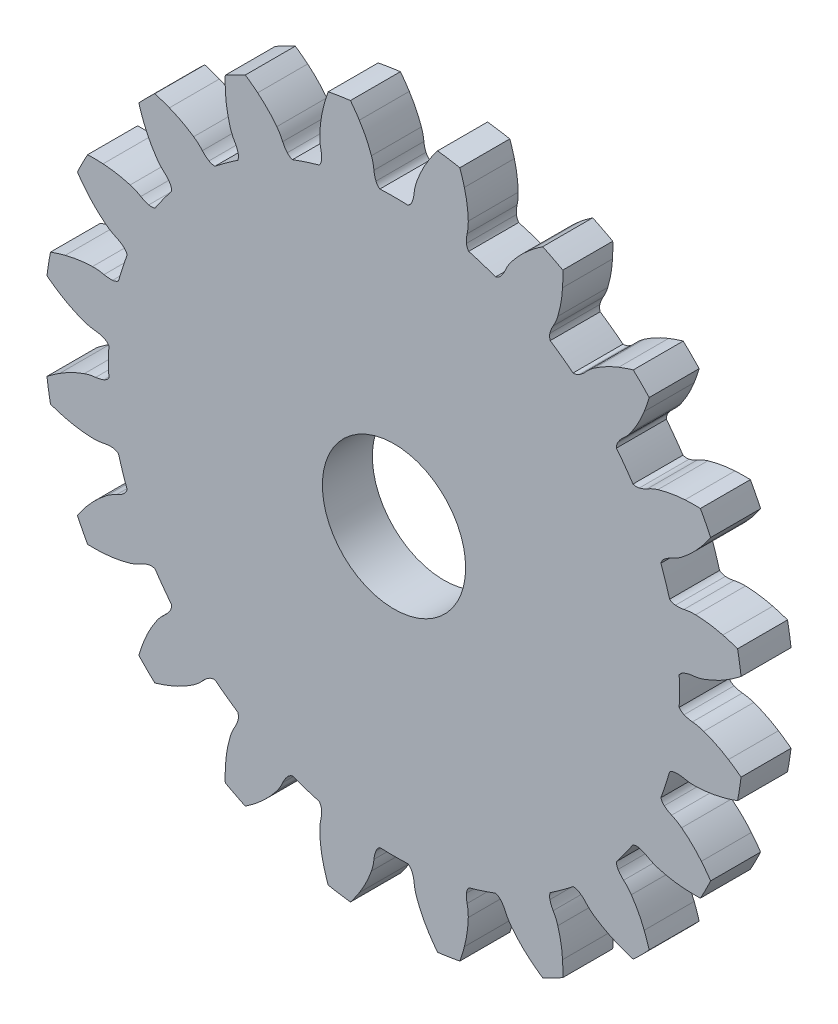
SolidWorks part; units mm, degrees
ref_plane "Front Plane" through (0, 0, 0) normal (0, 0, 1) x (1, 0, 0)
ref_plane "Top Plane" through (0, 0, 0) normal (0, 1, 0) x (1, 0, 0)
ref_plane "Right Plane" through (0, 0, 0) normal (1, 0, 0) x (0, 0, -1)
sketch "Model" plane through (0, 0, 0) normal (0, 0, 1) x (1, 0, 0)
  line L0 (-1.9599, -122.157) -> (1.9099, -120.8335)
  line L1 (1.9099, -120.8335) -> (1.9099, -119.1665)
  line L2 (1.9099, -119.1665) -> (-1.9599, -117.843)
  line L3 (-1.9599, -117.843) -> (-1.9599, -116.157)
  line L4 (-1.9599, -116.157) -> (1.9099, -114.8335)
  line L5 (1.9099, -114.8335) -> (1.9099, -113.1665)
  line L6 (1.9099, -113.1665) -> (-1.9599, -111.843)
  line L7 (-1.9599, -111.843) -> (-1.9599, -110.157)
  line L8 (-1.9599, -110.157) -> (1.9099, -108.8335)
  line L9 (1.9099, -108.8335) -> (1.9099, -107.1665)
  line L10 (1.9099, -107.1665) -> (-1.9599, -105.843)
  line L11 (-1.9599, -105.843) -> (-1.9599, -104.157)
  line L12 (-1.9599, -104.157) -> (1.9099, -102.8335)
  line L13 (1.9099, -102.8335) -> (1.9099, -101.1665)
  line L14 (1.9099, -101.1665) -> (-1.9599, -99.843)
  line L15 (-1.9599, -99.843) -> (-1.9599, -98.157)
  line L16 (-1.9599, -98.157) -> (1.9099, -96.8335)
  line L17 (1.9099, -96.8335) -> (1.9099, -95.1665)
  line L18 (1.9099, -95.1665) -> (-1.9599, -93.843)
  line L19 (-1.9599, -93.843) -> (-1.9599, -92.157)
  line L20 (-1.9599, -92.157) -> (1.9099, -90.8335)
  line L21 (1.9099, -90.8335) -> (1.9099, -89.1665)
  line L22 (1.9099, -89.1665) -> (-1.9599, -87.843)
  line L23 (-1.9599, -87.843) -> (-1.9599, -86.157)
  line L24 (-1.9599, -86.157) -> (1.9099, -84.8335)
  line L25 (1.9099, -84.8335) -> (1.9099, -83.1665)
  line L26 (1.9099, -83.1665) -> (-1.9599, -81.843)
  line L27 (-1.9599, -81.843) -> (-1.9599, -80.157)
  line L28 (-1.9599, -80.157) -> (1.9099, -78.8335)
  line L29 (1.9099, -78.8335) -> (1.9099, -77.1665)
  line L30 (1.9099, -77.1665) -> (-1.9599, -75.843)
  line L31 (-1.9599, -75.843) -> (-1.9599, -74.157)
  line L32 (-1.9599, -74.157) -> (1.9099, -72.8335)
  line L33 (1.9099, -72.8335) -> (1.9099, -71.1665)
  line L34 (1.9099, -71.1665) -> (-1.9599, -69.843)
  line L35 (-1.9599, -69.843) -> (-1.9599, -68.157)
  line L36 (-1.9599, -68.157) -> (1.9099, -66.8335)
  line L37 (1.9099, -66.8335) -> (1.9099, -65.1665)
  line L38 (1.9099, -65.1665) -> (-1.9599, -63.843)
  line L39 (-1.9599, -63.843) -> (-1.9599, -62.157)
  line L40 (-1.9599, -62.157) -> (1.9099, -60.8335)
  line L41 (1.9099, -60.8335) -> (1.9099, -59.1665)
  line L42 (1.9099, -59.1665) -> (-1.9599, -57.843)
  line L43 (-1.9599, -57.843) -> (-1.9599, -56.157)
  line L44 (-1.9599, -56.157) -> (1.9099, -54.8335)
  line L45 (1.9099, -54.8335) -> (1.9099, -53.1665)
  line L46 (1.9099, -53.1665) -> (-1.9599, -51.843)
  line L47 (-1.9599, -51.843) -> (-1.9599, -50.157)
  line L48 (-1.9599, -50.157) -> (1.9099, -48.8335)
  line L49 (1.9099, -48.8335) -> (1.9099, -47.1665)
  line L50 (1.9099, -47.1665) -> (-1.9599, -45.843)
  line L51 (-1.9599, -45.843) -> (-1.9599, -44.157)
  line L52 (-1.9599, -44.157) -> (1.9099, -42.8335)
  line L53 (1.9099, -42.8335) -> (1.9099, -41.1665)
  line L54 (1.9099, -41.1665) -> (-1.9599, -39.843)
  line L55 (-1.9599, -39.843) -> (-1.9599, -38.157)
  line L56 (-1.9599, -38.157) -> (1.9099, -36.8335)
  line L57 (1.9099, -36.8335) -> (1.9099, -35.1665)
  line L58 (1.9099, -35.1665) -> (-1.9599, -33.843)
  line L59 (-1.9599, -33.843) -> (-1.9599, -32.157)
  line L60 (-1.9599, -32.157) -> (1.9099, -30.8335)
  line L61 (1.9099, -30.8335) -> (1.9099, -29.1665)
  line L62 (1.9099, -29.1665) -> (-1.9599, -27.843)
  line L63 (-1.9599, -27.843) -> (-1.9599, -26.157)
  line L64 (-1.9599, -26.157) -> (1.9099, -24.8335)
  line L65 (1.9099, -24.8335) -> (1.9099, -23.1665)
  line L66 (1.9099, -23.1665) -> (-1.9599, -21.843)
  line L67 (-1.9599, -21.843) -> (-1.9599, -20.157)
  line L68 (-1.9599, -20.157) -> (1.9099, -18.8335)
  line L69 (1.9099, -18.8335) -> (1.9099, -17.1665)
  line L70 (1.9099, -17.1665) -> (-1.9599, -15.843)
  line L71 (-1.9599, -15.843) -> (-1.9599, -14.157)
  line L72 (-1.9599, -14.157) -> (1.9099, -12.8335)
  line L73 (1.9099, -12.8335) -> (1.9099, -11.1665)
  line L74 (1.9099, -11.1665) -> (-1.9599, -9.843)
  line L75 (-1.9599, -9.843) -> (-1.9599, -8.157)
  line L76 (-1.9599, -8.157) -> (1.9099, -6.8335)
  line L77 (1.9099, -6.8335) -> (1.9099, -5.1665)
  line L78 (1.9099, -5.1665) -> (-1.9599, -3.843)
  line L79 (-1.9599, -3.843) -> (-1.9599, -2.157)
  line L80 (-1.9599, -2.157) -> (1.9099, -0.8335)
  line L81 (1.9099, -0.8335) -> (1.9099, 0.8335)
  line L82 (1.9099, 0.8335) -> (-1.9599, 2.157)
  line L83 (-1.9599, 2.157) -> (-1.9599, 3.843)
  line L84 (-1.9599, 3.843) -> (1.9099, 5.1665)
  line L85 (1.9099, 5.1665) -> (1.9099, 6.8335)
  line L86 (1.9099, 6.8335) -> (-1.9599, 8.157)
  line L87 (-1.9599, 8.157) -> (-1.9599, 9.843)
  line L88 (-1.9599, 9.843) -> (1.9099, 11.1665)
  line L89 (1.9099, 11.1665) -> (1.9099, 12.8335)
  line L90 (1.9099, 12.8335) -> (-1.9599, 14.157)
  line L91 (-1.9599, 14.157) -> (-1.9599, 15.843)
  line L92 (-1.9599, 15.843) -> (1.9099, 17.1665)
  line L93 (1.9099, 17.1665) -> (1.9099, 18.8335)
  line L94 (1.9099, 18.8335) -> (-1.9599, 20.157)
  line L95 (-1.9599, 20.157) -> (-1.9599, 21.843)
  line L96 (-1.9599, 21.843) -> (1.9099, 23.1665)
  line L97 (1.9099, 23.1665) -> (1.9099, 24.8335)
  line L98 (1.9099, 24.8335) -> (-1.9599, 26.157)
  line L99 (-1.9599, 26.157) -> (-1.9599, 27.843)
  line L100 (-1.9599, 27.843) -> (1.9099, 29.1665)
  line L101 (1.9099, 29.1665) -> (1.9099, 30.8335)
  line L102 (1.9099, 30.8335) -> (-1.9599, 32.157)
  line L103 (-1.9599, 32.157) -> (-1.9599, 33.843)
  line L104 (-1.9599, 33.843) -> (1.9099, 35.1665)
  line L105 (1.9099, 35.1665) -> (1.9099, 36.8335)
  line L106 (1.9099, 36.8335) -> (-1.9599, 38.157)
  line L107 (-1.9599, 38.157) -> (-1.9599, 39.843)
  line L108 (-1.9599, 39.843) -> (1.9099, 41.1665)
  line L109 (1.9099, 41.1665) -> (1.9099, 42.8335)
  line L110 (1.9099, 42.8335) -> (-1.9599, 44.157)
  line L111 (-1.9599, 44.157) -> (-1.9599, 45.843)
  line L112 (-1.9599, 45.843) -> (1.9099, 47.1665)
  line L113 (1.9099, 47.1665) -> (1.9099, 48.8335)
  line L114 (1.9099, 48.8335) -> (-1.9599, 50.157)
  line L115 (-1.9599, 50.157) -> (-1.9599, 51.843)
  line L116 (-1.9599, 51.843) -> (1.9099, 53.1665)
  line L117 (1.9099, 53.1665) -> (1.9099, 54.8335)
  line L118 (1.9099, 54.8335) -> (-1.9599, 56.157)
  line L119 (-1.9599, 56.157) -> (-1.9599, 57.843)
  line L120 (-1.9599, 57.843) -> (1.9099, 59.1665)
  line L121 (1.9099, 59.1665) -> (1.9099, 60.8335)
  line L122 (1.9099, 60.8335) -> (-1.9599, 62.157)
  line L123 (-1.9599, 62.157) -> (-1.9599, 63.843)
  line L124 (-1.9599, 63.843) -> (1.9099, 65.1665)
  line L125 (1.9099, 65.1665) -> (1.9099, 66.8335)
  line L126 (1.9099, 66.8335) -> (-1.9599, 68.157)
  line L127 (-1.9599, 68.157) -> (-1.9599, 69.843)
  line L128 (-1.9599, 69.843) -> (1.9099, 71.1665)
  line L129 (1.9099, 71.1665) -> (1.9099, 72.8335)
  line L130 (1.9099, 72.8335) -> (-1.9599, 74.157)
  line L131 (-1.9599, 74.157) -> (-1.9599, 75.843)
  line L132 (-1.9599, 75.843) -> (1.9099, 77.1665)
  line L133 (1.9099, 77.1665) -> (1.9099, 78.8335)
  line L134 (1.9099, 78.8335) -> (-1.9599, 80.157)
  line L135 (-1.9599, 80.157) -> (-1.9599, 81.843)
  line L136 (-1.9599, 81.843) -> (1.9099, 83.1665)
  line L137 (1.9099, 83.1665) -> (1.9099, 84.8335)
  line L138 (1.9099, 84.8335) -> (-1.9599, 86.157)
  line L139 (-1.9599, 86.157) -> (-1.9599, 87.843)
  line L140 (-1.9599, 87.843) -> (1.9099, 89.1665)
  line L141 (1.9099, 89.1665) -> (1.9099, 90.8335)
  line L142 (1.9099, 90.8335) -> (-1.9599, 92.157)
  line L143 (-1.9599, 92.157) -> (-1.9599, 93.843)
  line L144 (-1.9599, 93.843) -> (1.9099, 95.1665)
  line L145 (1.9099, 95.1665) -> (1.9099, 96.8335)
  line L146 (1.9099, 96.8335) -> (-1.9599, 98.157)
  line L147 (-1.9599, 98.157) -> (-1.9599, 99.843)
  line L148 (-1.9599, 99.843) -> (1.9099, 101.1665)
  line L149 (1.9099, 101.1665) -> (1.9099, 102.8335)
  line L150 (1.9099, 102.8335) -> (-1.9599, 104.157)
  line L151 (-1.9599, 104.157) -> (-1.9599, 105.843)
  line L152 (-1.9599, 105.843) -> (1.9099, 107.1665)
  line L153 (1.9099, 107.1665) -> (1.9099, 108.8335)
  line L154 (1.9099, 108.8335) -> (-1.9599, 110.157)
  line L155 (-1.9599, 110.157) -> (-1.9599, 111.843)
  line L156 (-1.9599, 111.843) -> (1.9099, 113.1665)
  line L157 (1.9099, 113.1665) -> (1.9099, 114.8335)
  line L158 (1.9099, 114.8335) -> (-1.9599, 116.157)
  line L159 (-1.9599, 116.157) -> (-1.9599, 117.843)
  line L160 (-1.9599, 117.843) -> (1.9099, 119.1665)
  line L161 (1.9099, 119.1665) -> (1.9099, 120.8335)
  line L162 (1.9099, 120.8335) -> (-1.9599, 122.157)
  line L163 (-1.9599, 122.157) -> (-1.9599, 123)
  line L164 (-1.9599, 123) -> (-9.5993, 123)
  line L165 (-9.5993, 123) -> (-9.5993, -123)
  line L166 (-9.5993, -123) -> (-1.9599, -123)
  line L167 (-1.9599, -123) -> (-1.9599, -122.157)
  line L168 (-1.5377, 3.9366) -> (-1.6512, 3.2864)
  line L169 (-1.6512, 3.2864) -> (-1.7442, 2.6331)
  line L170 (-1.7442, 2.6331) -> (-1.7455, 2.6215)
  line L171 (-1.7455, 2.6215) -> (-1.7388, 2.6161)
  line L172 (-1.7388, 2.6161) -> (-1.4771, 2.4198)
  line L173 (-1.4771, 2.4198) -> (-1.2239, 2.242)
  line L174 (-1.2239, 2.242) -> (-0.9803, 2.082)
  line L175 (-0.9803, 2.082) -> (-0.7469, 1.9391)
  line L176 (-0.7469, 1.9391) -> (-0.5246, 1.8124)
  line L177 (-0.5246, 1.8124) -> (-0.3143, 1.7011)
  line L178 (-0.3143, 1.7011) -> (-0.1165, 1.6044)
  line L179 (-0.1165, 1.6044) -> (0.0679, 1.5212)
  line L180 (0.0679, 1.5212) -> (0.2383, 1.4506)
  line L181 (0.2383, 1.4506) -> (0.3942, 1.3918)
  line L182 (0.3942, 1.3918) -> (0.535, 1.3436)
  line L183 (0.535, 1.3436) -> (0.6602, 1.3051)
  line L184 (0.6602, 1.3051) -> (0.7694, 1.2753)
  line L185 (0.7694, 1.2753) -> (0.862, 1.2531)
  line L186 (0.862, 1.2531) -> (0.9379, 1.2374)
  line L187 (0.9379, 1.2374) -> (0.9966, 1.2272)
  line L188 (0.9966, 1.2272) -> (1.038, 1.2213)
  line L189 (1.038, 1.2213) -> (1.0618, 1.2187)
  line L190 (1.0618, 1.2187) -> (1.0916, 1.2164)
  line L191 (1.0916, 1.2164) -> (1.2696, 1.1958)
  line L192 (1.2696, 1.1958) -> (1.4284, 1.1659)
  line L193 (1.4284, 1.1659) -> (1.5676, 1.1277)
  line L194 (1.5676, 1.1277) -> (1.6869, 1.0826)
  line L195 (1.6869, 1.0826) -> (1.7859, 1.0316)
  line L196 (1.7859, 1.0316) -> (1.8646, 0.9761)
  line L197 (1.8646, 0.9761) -> (1.9226, 0.9172)
  line L198 (1.9226, 0.9172) -> (1.9599, 0.8563)
  line L199 (1.9599, 0.8563) -> (1.9764, 0.7945)
  line L200 (1.9764, 0.7945) -> (1.9599, 0.2692)
  line L201 (1.9599, 0.2692) -> (1.9599, -0.2692)
  line L202 (1.9599, -0.2692) -> (1.9764, -0.7945)
  line L203 (1.9764, -0.7945) -> (1.9599, -0.8563)
  line L204 (1.9599, -0.8563) -> (1.9226, -0.9172)
  line L205 (1.9226, -0.9172) -> (1.8646, -0.9761)
  line L206 (1.8646, -0.9761) -> (1.7859, -1.0316)
  line L207 (1.7859, -1.0316) -> (1.6869, -1.0826)
  line L208 (1.6869, -1.0826) -> (1.5676, -1.1277)
  line L209 (1.5676, -1.1277) -> (1.4284, -1.1659)
  line L210 (1.4284, -1.1659) -> (1.2696, -1.1958)
  line L211 (1.2696, -1.1958) -> (1.0916, -1.2164)
  line L212 (1.0916, -1.2164) -> (1.0618, -1.2187)
  line L213 (1.0618, -1.2187) -> (1.038, -1.2213)
  line L214 (1.038, -1.2213) -> (0.9966, -1.2272)
  line L215 (0.9966, -1.2272) -> (0.9379, -1.2374)
  line L216 (0.9379, -1.2374) -> (0.862, -1.2531)
  line L217 (0.862, -1.2531) -> (0.7694, -1.2753)
  line L218 (0.7694, -1.2753) -> (0.6602, -1.3051)
  line L219 (0.6602, -1.3051) -> (0.535, -1.3436)
  line L220 (0.535, -1.3436) -> (0.3942, -1.3918)
  line L221 (0.3942, -1.3918) -> (0.2383, -1.4506)
  line L222 (0.2383, -1.4506) -> (0.0679, -1.5212)
  line L223 (0.0679, -1.5212) -> (-0.1165, -1.6044)
  line L224 (-0.1165, -1.6044) -> (-0.3143, -1.7011)
  line L225 (-0.3143, -1.7011) -> (-0.5246, -1.8124)
  line L226 (-0.5246, -1.8124) -> (-0.7469, -1.9391)
  line L227 (-0.7469, -1.9391) -> (-0.9803, -2.082)
  line L228 (-0.9803, -2.082) -> (-1.2239, -2.242)
  line L229 (-1.2239, -2.242) -> (-1.4771, -2.4198)
  line L230 (-1.4771, -2.4198) -> (-1.7388, -2.6161)
  line L231 (-1.7388, -2.6161) -> (-1.7455, -2.6215)
  line L232 (-1.7455, -2.6215) -> (-1.7442, -2.6331)
  line L233 (-1.7442, -2.6331) -> (-1.6512, -3.2864)
  line L234 (-1.6512, -3.2864) -> (-1.5377, -3.9366)
  line L235 (-1.5377, -3.9366) -> (-1.5354, -3.948)
  line L236 (-1.5354, -3.948) -> (-1.5274, -3.951)
  line L237 (-1.5274, -3.951) -> (-1.2178, -4.0569)
  line L238 (-1.2178, -4.0569) -> (-0.9221, -4.1477)
  line L239 (-0.9221, -4.1477) -> (-0.6409, -4.2246)
  line L240 (-0.6409, -4.2246) -> (-0.3748, -4.2884)
  line L241 (-0.3748, -4.2884) -> (-0.1243, -4.3402)
  line L242 (-0.1243, -4.3402) -> (0.1102, -4.381)
  line L243 (0.1102, -4.381) -> (0.3281, -4.412)
  line L244 (0.3281, -4.412) -> (0.5292, -4.4341)
  line L245 (0.5292, -4.4341) -> (0.7132, -4.4485)
  line L246 (0.7132, -4.4485) -> (0.8796, -4.4563)
  line L247 (0.8796, -4.4563) -> (1.0284, -4.4586)
  line L248 (1.0284, -4.4586) -> (1.1593, -4.4565)
  line L249 (1.1593, -4.4565) -> (1.2724, -4.4511)
  line L250 (1.2724, -4.4511) -> (1.3673, -4.4436)
  line L251 (1.3673, -4.4436) -> (1.4443, -4.4351)
  line L252 (1.4443, -4.4351) -> (1.5034, -4.4267)
  line L253 (1.5034, -4.4267) -> (1.5445, -4.4195)
  line L254 (1.5445, -4.4195) -> (1.568, -4.4146)
  line L255 (1.568, -4.4146) -> (1.5971, -4.4076)
  line L256 (1.5971, -4.4076) -> (1.7727, -4.3722)
  line L257 (1.7727, -4.3722) -> (1.933, -4.3516)
  line L258 (1.933, -4.3516) -> (2.0771, -4.3448)
  line L259 (2.0771, -4.3448) -> (2.2045, -4.3509)
  line L260 (2.2045, -4.3509) -> (2.3145, -4.3688)
  line L261 (2.3145, -4.3688) -> (2.4064, -4.3973)
  line L262 (2.4064, -4.3973) -> (2.4798, -4.4353)
  line L263 (2.4798, -4.4353) -> (2.5341, -4.4818)
  line L264 (2.5341, -4.4818) -> (2.5689, -4.5354)
  line L265 (2.5689, -4.5354) -> (2.7155, -5.0401)
  line L266 (2.7155, -5.0401) -> (2.8819, -5.5522)
  line L267 (2.8819, -5.5522) -> (3.0599, -6.0467)
  line L268 (3.0599, -6.0467) -> (3.0633, -6.1105)
  line L269 (3.0633, -6.1105) -> (3.0467, -6.18)
  line L270 (3.0467, -6.18) -> (3.0097, -6.2539)
  line L271 (3.0097, -6.2539) -> (2.9521, -6.331)
  line L272 (2.9521, -6.331) -> (2.8736, -6.4101)
  line L273 (2.8736, -6.4101) -> (2.7741, -6.4899)
  line L274 (2.7741, -6.4899) -> (2.6535, -6.5692)
  line L275 (2.6535, -6.5692) -> (2.5118, -6.6468)
  line L276 (2.5118, -6.6468) -> (2.3488, -6.7213)
  line L277 (2.3488, -6.7213) -> (2.3212, -6.7327)
  line L278 (2.3212, -6.7327) -> (2.2993, -6.7426)
  line L279 (2.2993, -6.7426) -> (2.2618, -6.761)
  line L280 (2.2618, -6.761) -> (2.2091, -6.7888)
  line L281 (2.2091, -6.7888) -> (2.1418, -6.8272)
  line L282 (2.1418, -6.8272) -> (2.0605, -6.877)
  line L283 (2.0605, -6.877) -> (1.966, -6.939)
  line L284 (1.966, -6.939) -> (1.8588, -7.0143)
  line L285 (1.8588, -7.0143) -> (1.7398, -7.1036)
  line L286 (1.7398, -7.1036) -> (1.6097, -7.2078)
  line L287 (1.6097, -7.2078) -> (1.4694, -7.3275)
  line L288 (1.4694, -7.3275) -> (1.3197, -7.4636)
  line L289 (1.3197, -7.4636) -> (1.1616, -7.6168)
  line L290 (1.1616, -7.6168) -> (0.9959, -7.7876)
  line L291 (0.9959, -7.7876) -> (0.8236, -7.9768)
  line L292 (0.8236, -7.9768) -> (0.6459, -8.1848)
  line L293 (0.6459, -8.1848) -> (0.4635, -8.4123)
  line L294 (0.4635, -8.4123) -> (0.2777, -8.6596)
  line L295 (0.2777, -8.6596) -> (0.0895, -8.9272)
  line L296 (0.0895, -8.9272) -> (0.0848, -8.9344)
  line L297 (0.0848, -8.9344) -> (0.0896, -8.945)
  line L298 (0.0896, -8.945) -> (0.3799, -9.5376)
  line L299 (0.3799, -9.5376) -> (0.6887, -10.1209)
  line L300 (0.6887, -10.1209) -> (0.6945, -10.131)
  line L301 (0.6945, -10.131) -> (0.7031, -10.1314)
  line L302 (0.7031, -10.1314) -> (1.0302, -10.1364)
  line L303 (1.0302, -10.1364) -> (1.3395, -10.1315)
  line L304 (1.3395, -10.1315) -> (1.6307, -10.1177)
  line L305 (1.6307, -10.1177) -> (1.9035, -10.0961)
  line L306 (1.9035, -10.0961) -> (2.1578, -10.0679)
  line L307 (2.1578, -10.0679) -> (2.3934, -10.0343)
  line L308 (2.3934, -10.0343) -> (2.6102, -9.9964)
  line L309 (2.6102, -9.9964) -> (2.8083, -9.9553)
  line L310 (2.8083, -9.9553) -> (2.9877, -9.9122)
  line L311 (2.9877, -9.9122) -> (3.1484, -9.8682)
  line L312 (3.1484, -9.8682) -> (3.2906, -9.8244)
  line L313 (3.2906, -9.8244) -> (3.4145, -9.7819)
  line L314 (3.4145, -9.7819) -> (3.5203, -9.7419)
  line L315 (3.5203, -9.7419) -> (3.6083, -9.7054)
  line L316 (3.6083, -9.7054) -> (3.6789, -9.6735)
  line L317 (3.6789, -9.6735) -> (3.7324, -9.6473)
  line L318 (3.7324, -9.6473) -> (3.7694, -9.6277)
  line L319 (3.7694, -9.6277) -> (3.7902, -9.6158)
  line L320 (3.7902, -9.6158) -> (3.8157, -9.6002)
  line L321 (3.8157, -9.6002) -> (3.9718, -9.5122)
  line L322 (3.9718, -9.5122) -> (4.1178, -9.4431)
  line L323 (4.1178, -9.4431) -> (4.2529, -9.3921)
  line L324 (4.2529, -9.3921) -> (4.3759, -9.3585)
  line L325 (4.3759, -9.3585) -> (4.486, -9.3415)
  line L326 (4.486, -9.3415) -> (4.5822, -9.3402)
  line L327 (4.5822, -9.3402) -> (4.6638, -9.3538)
  line L328 (4.6638, -9.3538) -> (4.7297, -9.3811)
  line L329 (4.7297, -9.3811) -> (4.7794, -9.4214)
  line L330 (4.7794, -9.4214) -> (5.0748, -9.8561)
  line L331 (5.0748, -9.8561) -> (5.3913, -10.2917)
  line L332 (5.3913, -10.2917) -> (5.7134, -10.707)
  line L333 (5.7134, -10.707) -> (5.7364, -10.7667)
  line L334 (5.7364, -10.7667) -> (5.742, -10.8379)
  line L335 (5.742, -10.8379) -> (5.7297, -10.9196)
  line L336 (5.7297, -10.9196) -> (5.6987, -11.0107)
  line L337 (5.6987, -11.0107) -> (5.6485, -11.1102)
  line L338 (5.6485, -11.1102) -> (5.5786, -11.2168)
  line L339 (5.5786, -11.2168) -> (5.4884, -11.3295)
  line L340 (5.4884, -11.3295) -> (5.3775, -11.447)
  line L341 (5.3775, -11.447) -> (5.2456, -11.5683)
  line L342 (5.2456, -11.5683) -> (5.2228, -11.5877)
  line L343 (5.2228, -11.5877) -> (5.2051, -11.6038)
  line L344 (5.2051, -11.6038) -> (5.1751, -11.6329)
  line L345 (5.1751, -11.6329) -> (5.1336, -11.6757)
  line L346 (5.1336, -11.6757) -> (5.0815, -11.733)
  line L347 (5.0815, -11.733) -> (5.0195, -11.8054)
  line L348 (5.0195, -11.8054) -> (4.9488, -11.8937)
  line L349 (4.9488, -11.8937) -> (4.8701, -11.9984)
  line L350 (4.8701, -11.9984) -> (4.7845, -12.1201)
  line L351 (4.7845, -12.1201) -> (4.693, -12.2594)
  line L352 (4.693, -12.2594) -> (4.5965, -12.4166)
  line L353 (4.5965, -12.4166) -> (4.4962, -12.5923)
  line L354 (4.4962, -12.5923) -> (4.3932, -12.7868)
  line L355 (4.3932, -12.7868) -> (4.2884, -13.0005)
  line L356 (4.2884, -13.0005) -> (4.1831, -13.2337)
  line L357 (4.1831, -13.2337) -> (4.0782, -13.4865)
  line L358 (4.0782, -13.4865) -> (3.9751, -13.7591)
  line L359 (3.9751, -13.7591) -> (3.8748, -14.0517)
  line L360 (3.8748, -14.0517) -> (3.7785, -14.3644)
  line L361 (3.7785, -14.3644) -> (3.7763, -14.3727)
  line L362 (3.7763, -14.3727) -> (3.7841, -14.3813)
  line L363 (3.7841, -14.3813) -> (4.2434, -14.8552)
  line L364 (4.2434, -14.8552) -> (4.7173, -15.3145)
  line L365 (4.7173, -15.3145) -> (4.7259, -15.3223)
  line L366 (4.7259, -15.3223) -> (4.7342, -15.3201)
  line L367 (4.7342, -15.3201) -> (5.0469, -15.2238)
  line L368 (5.0469, -15.2238) -> (5.3395, -15.1235)
  line L369 (5.3395, -15.1235) -> (5.6121, -15.0203)
  line L370 (5.6121, -15.0203) -> (5.8649, -14.9155)
  line L371 (5.8649, -14.9155) -> (6.0981, -14.8102)
  line L372 (6.0981, -14.8102) -> (6.3117, -14.7054)
  line L373 (6.3117, -14.7054) -> (6.5063, -14.6023)
  line L374 (6.5063, -14.6023) -> (6.682, -14.5021)
  line L375 (6.682, -14.5021) -> (6.8392, -14.4056)
  line L376 (6.8392, -14.4056) -> (6.9785, -14.3141)
  line L377 (6.9785, -14.3141) -> (7.1002, -14.2285)
  line L378 (7.1002, -14.2285) -> (7.2049, -14.1498)
  line L379 (7.2049, -14.1498) -> (7.2932, -14.0791)
  line L380 (7.2932, -14.0791) -> (7.3656, -14.0171)
  line L381 (7.3656, -14.0171) -> (7.4229, -13.965)
  line L382 (7.4229, -13.965) -> (7.4657, -13.9235)
  line L383 (7.4657, -13.9235) -> (7.4948, -13.8935)
  line L384 (7.4948, -13.8935) -> (7.5109, -13.8758)
  line L385 (7.5109, -13.8758) -> (7.5303, -13.853)
  line L386 (7.5303, -13.853) -> (7.6515, -13.7211)
  line L387 (7.6515, -13.7211) -> (7.7691, -13.6102)
  line L388 (7.7691, -13.6102) -> (7.8818, -13.52)
  line L389 (7.8818, -13.52) -> (7.9884, -13.4501)
  line L390 (7.9884, -13.4501) -> (8.0879, -13.3999)
  line L391 (8.0879, -13.3999) -> (8.179, -13.3689)
  line L392 (8.179, -13.3689) -> (8.2607, -13.3566)
  line L393 (8.2607, -13.3566) -> (8.3319, -13.3622)
  line L394 (8.3319, -13.3622) -> (8.3916, -13.3852)
  line L395 (8.3916, -13.3852) -> (8.8069, -13.7073)
  line L396 (8.8069, -13.7073) -> (9.2425, -14.0238)
  line L397 (9.2425, -14.0238) -> (9.6772, -14.3192)
  line L398 (9.6772, -14.3192) -> (9.7175, -14.3688)
  line L399 (9.7175, -14.3688) -> (9.7448, -14.4348)
  line L400 (9.7448, -14.4348) -> (9.7584, -14.5164)
  line L401 (9.7584, -14.5164) -> (9.7571, -14.6126)
  line L402 (9.7571, -14.6126) -> (9.7401, -14.7227)
  line L403 (9.7401, -14.7227) -> (9.7065, -14.8457)
  line L404 (9.7065, -14.8457) -> (9.6555, -14.9808)
  line L405 (9.6555, -14.9808) -> (9.5864, -15.1268)
  line L406 (9.5864, -15.1268) -> (9.4984, -15.2829)
  line L407 (9.4984, -15.2829) -> (9.4828, -15.3084)
  line L408 (9.4828, -15.3084) -> (9.4709, -15.3292)
  line L409 (9.4709, -15.3292) -> (9.4513, -15.3661)
  line L410 (9.4513, -15.3661) -> (9.4251, -15.4197)
  line L411 (9.4251, -15.4197) -> (9.3932, -15.4903)
  line L412 (9.3932, -15.4903) -> (9.3567, -15.5783)
  line L413 (9.3567, -15.5783) -> (9.3167, -15.6841)
  line L414 (9.3167, -15.6841) -> (9.2742, -15.808)
  line L415 (9.2742, -15.808) -> (9.2304, -15.9502)
  line L416 (9.2304, -15.9502) -> (9.1864, -16.1109)
  line L417 (9.1864, -16.1109) -> (9.1433, -16.2903)
  line L418 (9.1433, -16.2903) -> (9.1022, -16.4884)
  line L419 (9.1022, -16.4884) -> (9.0643, -16.7052)
  line L420 (9.0643, -16.7052) -> (9.0307, -16.9408)
  line L421 (9.0307, -16.9408) -> (9.0025, -17.1951)
  line L422 (9.0025, -17.1951) -> (8.9809, -17.4679)
  line L423 (8.9809, -17.4679) -> (8.9671, -17.7591)
  line L424 (8.9671, -17.7591) -> (8.9622, -18.0684)
  line L425 (8.9622, -18.0684) -> (8.9672, -18.3955)
  line L426 (8.9672, -18.3955) -> (8.9676, -18.4041)
  line L427 (8.9676, -18.4041) -> (8.9777, -18.4098)
  line L428 (8.9777, -18.4098) -> (9.561, -18.7187)
  line L429 (9.561, -18.7187) -> (10.1536, -19.009)
  line L430 (10.1536, -19.009) -> (10.1642, -19.0138)
  line L431 (10.1642, -19.0138) -> (10.1714, -19.0091)
  line L432 (10.1714, -19.0091) -> (10.439, -18.8209)
  line L433 (10.439, -18.8209) -> (10.6863, -18.6351)
  line L434 (10.6863, -18.6351) -> (10.9138, -18.4527)
  line L435 (10.9138, -18.4527) -> (11.1218, -18.2749)
  line L436 (11.1218, -18.2749) -> (11.311, -18.1027)
  line L437 (11.311, -18.1027) -> (11.4818, -17.937)
  line L438 (11.4818, -17.937) -> (11.635, -17.7789)
  line L439 (11.635, -17.7789) -> (11.7711, -17.6292)
  line L440 (11.7711, -17.6292) -> (11.8908, -17.4889)
  line L441 (11.8908, -17.4889) -> (11.995, -17.3588)
  line L442 (11.995, -17.3588) -> (12.0843, -17.2398)
  line L443 (12.0843, -17.2398) -> (12.1596, -17.1326)
  line L444 (12.1596, -17.1326) -> (12.2216, -17.038)
  line L445 (12.2216, -17.038) -> (12.2714, -16.9568)
  line L446 (12.2714, -16.9568) -> (12.3098, -16.8895)
  line L447 (12.3098, -16.8895) -> (12.3376, -16.8368)
  line L448 (12.3376, -16.8368) -> (12.356, -16.7993)
  line L449 (12.356, -16.7993) -> (12.3659, -16.7774)
  line L450 (12.3659, -16.7774) -> (12.3773, -16.7498)
  line L451 (12.3773, -16.7498) -> (12.4518, -16.5868)
  line L452 (12.4518, -16.5868) -> (12.5294, -16.4451)
  line L453 (12.5294, -16.4451) -> (12.6087, -16.3245)
  line L454 (12.6087, -16.3245) -> (12.6885, -16.225)
  line L455 (12.6885, -16.225) -> (12.7676, -16.1465)
  line L456 (12.7676, -16.1465) -> (12.8447, -16.0889)
  line L457 (12.8447, -16.0889) -> (12.9186, -16.0519)
  line L458 (12.9186, -16.0519) -> (12.9881, -16.0353)
  line L459 (12.9881, -16.0353) -> (13.0519, -16.0387)
  line L460 (13.0519, -16.0387) -> (13.5464, -16.2167)
  line L461 (13.5464, -16.2167) -> (14.0585, -16.3831)
  line L462 (14.0585, -16.3831) -> (14.5632, -16.5297)
  line L463 (14.5632, -16.5297) -> (14.6168, -16.5645)
  line L464 (14.6168, -16.5645) -> (14.6633, -16.6188)
  line L465 (14.6633, -16.6188) -> (14.7013, -16.6922)
  line L466 (14.7013, -16.6922) -> (14.7298, -16.7841)
  line L467 (14.7298, -16.7841) -> (14.7477, -16.8941)
  line L468 (14.7477, -16.8941) -> (14.7538, -17.0214)
  line L469 (14.7538, -17.0214) -> (14.747, -17.1656)
  line L470 (14.747, -17.1656) -> (14.7264, -17.3259)
  line L471 (14.7264, -17.3259) -> (14.691, -17.5015)
  line L472 (14.691, -17.5015) -> (14.684, -17.5306)
  line L473 (14.684, -17.5306) -> (14.6791, -17.5541)
  line L474 (14.6791, -17.5541) -> (14.6719, -17.5952)
  line L475 (14.6719, -17.5952) -> (14.6635, -17.6543)
  line L476 (14.6635, -17.6543) -> (14.655, -17.7312)
  line L477 (14.655, -17.7312) -> (14.6475, -17.8262)
  line L478 (14.6475, -17.8262) -> (14.6421, -17.9392)
  line L479 (14.6421, -17.9392) -> (14.64, -18.0702)
  line L480 (14.64, -18.0702) -> (14.6423, -18.219)
  line L481 (14.6423, -18.219) -> (14.6501, -18.3854)
  line L482 (14.6501, -18.3854) -> (14.6645, -18.5693)
  line L483 (14.6645, -18.5693) -> (14.6866, -18.7704)
  line L484 (14.6866, -18.7704) -> (14.7176, -18.9884)
  line L485 (14.7176, -18.9884) -> (14.7584, -19.2229)
  line L486 (14.7584, -19.2229) -> (14.8102, -19.4734)
  line L487 (14.8102, -19.4734) -> (14.874, -19.7395)
  line L488 (14.874, -19.7395) -> (14.9508, -20.0207)
  line L489 (14.9508, -20.0207) -> (15.0417, -20.3164)
  line L490 (15.0417, -20.3164) -> (15.1476, -20.6259)
  line L491 (15.1476, -20.6259) -> (15.1506, -20.634)
  line L492 (15.1506, -20.634) -> (15.162, -20.6363)
  line L493 (15.162, -20.6363) -> (15.8121, -20.7498)
  line L494 (15.8121, -20.7498) -> (16.4655, -20.8428)
  line L495 (16.4655, -20.8428) -> (16.4771, -20.8441)
  line L496 (16.4771, -20.8441) -> (16.4825, -20.8374)
  line L497 (16.4825, -20.8374) -> (16.6788, -20.5757)
  line L498 (16.6788, -20.5757) -> (16.8566, -20.3225)
  line L499 (16.8566, -20.3225) -> (17.0166, -20.0789)
  line L500 (17.0166, -20.0789) -> (17.1595, -19.8455)
  line L501 (17.1595, -19.8455) -> (17.2862, -19.6232)
  line L502 (17.2862, -19.6232) -> (17.3974, -19.4129)
  line L503 (17.3974, -19.4129) -> (17.4942, -19.2151)
  line L504 (17.4942, -19.2151) -> (17.5774, -19.0307)
  line L505 (17.5774, -19.0307) -> (17.648, -18.8603)
  line L506 (17.648, -18.8603) -> (17.7068, -18.7044)
  line L507 (17.7068, -18.7044) -> (17.755, -18.5636)
  line L508 (17.755, -18.5636) -> (17.7935, -18.4384)
  line L509 (17.7935, -18.4384) -> (17.8233, -18.3292)
  line L510 (17.8233, -18.3292) -> (17.8455, -18.2366)
  line L511 (17.8455, -18.2366) -> (17.8612, -18.1607)
  line L512 (17.8612, -18.1607) -> (17.8714, -18.102)
  line L513 (17.8714, -18.102) -> (17.8773, -18.0606)
  line L514 (17.8773, -18.0606) -> (17.8799, -18.0368)
  line L515 (17.8799, -18.0368) -> (17.8822, -18.007)
  line L516 (17.8822, -18.007) -> (17.9028, -17.829)
  line L517 (17.9028, -17.829) -> (17.9327, -17.6702)
  line L518 (17.9327, -17.6702) -> (17.9709, -17.531)
  line L519 (17.9709, -17.531) -> (18.016, -17.4117)
  line L520 (18.016, -17.4117) -> (18.067, -17.3127)
  line L521 (18.067, -17.3127) -> (18.1225, -17.234)
  line L522 (18.1225, -17.234) -> (18.1814, -17.176)
  line L523 (18.1814, -17.176) -> (18.2423, -17.1387)
  line L524 (18.2423, -17.1387) -> (18.3041, -17.1222)
  line L525 (18.3041, -17.1222) -> (18.8294, -17.1387)
  line L526 (18.8294, -17.1387) -> (19.3678, -17.1387)
  line L527 (19.3678, -17.1387) -> (19.8931, -17.1222)
  line L528 (19.8931, -17.1222) -> (19.9549, -17.1387)
  line L529 (19.9549, -17.1387) -> (20.0158, -17.176)
  line L530 (20.0158, -17.176) -> (20.0747, -17.234)
  line L531 (20.0747, -17.234) -> (20.1302, -17.3127)
  line L532 (20.1302, -17.3127) -> (20.1812, -17.4117)
  line L533 (20.1812, -17.4117) -> (20.2263, -17.531)
  line L534 (20.2263, -17.531) -> (20.2645, -17.6702)
  line L535 (20.2645, -17.6702) -> (20.2944, -17.829)
  line L536 (20.2944, -17.829) -> (20.315, -18.007)
  line L537 (20.315, -18.007) -> (20.3173, -18.0368)
  line L538 (20.3173, -18.0368) -> (20.3199, -18.0606)
  line L539 (20.3199, -18.0606) -> (20.3258, -18.102)
  line L540 (20.3258, -18.102) -> (20.336, -18.1607)
  line L541 (20.336, -18.1607) -> (20.3517, -18.2366)
  line L542 (20.3517, -18.2366) -> (20.3739, -18.3292)
  line L543 (20.3739, -18.3292) -> (20.4037, -18.4384)
  line L544 (20.4037, -18.4384) -> (20.4422, -18.5636)
  line L545 (20.4422, -18.5636) -> (20.4904, -18.7044)
  line L546 (20.4904, -18.7044) -> (20.5492, -18.8603)
  line L547 (20.5492, -18.8603) -> (20.6198, -19.0307)
  line L548 (20.6198, -19.0307) -> (20.703, -19.2151)
  line L549 (20.703, -19.2151) -> (20.7997, -19.4129)
  line L550 (20.7997, -19.4129) -> (20.911, -19.6232)
  line L551 (20.911, -19.6232) -> (21.0377, -19.8455)
  line L552 (21.0377, -19.8455) -> (21.1806, -20.0789)
  line L553 (21.1806, -20.0789) -> (21.3406, -20.3225)
  line L554 (21.3406, -20.3225) -> (21.5184, -20.5757)
  line L555 (21.5184, -20.5757) -> (21.7147, -20.8374)
  line L556 (21.7147, -20.8374) -> (21.7201, -20.8441)
  line L557 (21.7201, -20.8441) -> (21.7317, -20.8428)
  line L558 (21.7317, -20.8428) -> (22.385, -20.7498)
  line L559 (22.385, -20.7498) -> (23.0352, -20.6363)
  line L560 (23.0352, -20.6363) -> (23.0466, -20.634)
  line L561 (23.0466, -20.634) -> (23.0496, -20.6259)
  line L562 (23.0496, -20.6259) -> (23.1555, -20.3164)
  line L563 (23.1555, -20.3164) -> (23.2463, -20.0207)
  line L564 (23.2463, -20.0207) -> (23.3232, -19.7395)
  line L565 (23.3232, -19.7395) -> (23.387, -19.4734)
  line L566 (23.387, -19.4734) -> (23.4388, -19.2229)
  line L567 (23.4388, -19.2229) -> (23.4796, -18.9884)
  line L568 (23.4796, -18.9884) -> (23.5106, -18.7704)
  line L569 (23.5106, -18.7704) -> (23.5327, -18.5693)
  line L570 (23.5327, -18.5693) -> (23.5471, -18.3854)
  line L571 (23.5471, -18.3854) -> (23.5549, -18.219)
  line L572 (23.5549, -18.219) -> (23.5572, -18.0702)
  line L573 (23.5572, -18.0702) -> (23.5551, -17.9392)
  line L574 (23.5551, -17.9392) -> (23.5497, -17.8262)
  line L575 (23.5497, -17.8262) -> (23.5422, -17.7312)
  line L576 (23.5422, -17.7312) -> (23.5337, -17.6543)
  line L577 (23.5337, -17.6543) -> (23.5253, -17.5952)
  line L578 (23.5253, -17.5952) -> (23.5181, -17.5541)
  line L579 (23.5181, -17.5541) -> (23.5132, -17.5306)
  line L580 (23.5132, -17.5306) -> (23.5062, -17.5015)
  line L581 (23.5062, -17.5015) -> (23.4708, -17.3259)
  line L582 (23.4708, -17.3259) -> (23.4502, -17.1656)
  line L583 (23.4502, -17.1656) -> (23.4434, -17.0214)
  line L584 (23.4434, -17.0214) -> (23.4495, -16.8941)
  line L585 (23.4495, -16.8941) -> (23.4674, -16.7841)
  line L586 (23.4674, -16.7841) -> (23.4959, -16.6922)
  line L587 (23.4959, -16.6922) -> (23.5339, -16.6188)
  line L588 (23.5339, -16.6188) -> (23.5804, -16.5645)
  line L589 (23.5804, -16.5645) -> (23.634, -16.5297)
  line L590 (23.634, -16.5297) -> (24.1387, -16.3831)
  line L591 (24.1387, -16.3831) -> (24.6508, -16.2167)
  line L592 (24.6508, -16.2167) -> (25.1453, -16.0387)
  line L593 (25.1453, -16.0387) -> (25.2091, -16.0353)
  line L594 (25.2091, -16.0353) -> (25.2786, -16.0519)
  line L595 (25.2786, -16.0519) -> (25.3525, -16.0889)
  line L596 (25.3525, -16.0889) -> (25.4296, -16.1465)
  line L597 (25.4296, -16.1465) -> (25.5087, -16.225)
  line L598 (25.5087, -16.225) -> (25.5885, -16.3245)
  line L599 (25.5885, -16.3245) -> (25.6678, -16.4451)
  line L600 (25.6678, -16.4451) -> (25.7453, -16.5868)
  line L601 (25.7453, -16.5868) -> (25.8199, -16.7498)
  line L602 (25.8199, -16.7498) -> (25.8313, -16.7774)
  line L603 (25.8313, -16.7774) -> (25.8412, -16.7993)
  line L604 (25.8412, -16.7993) -> (25.8595, -16.8368)
  line L605 (25.8595, -16.8368) -> (25.8874, -16.8895)
  line L606 (25.8874, -16.8895) -> (25.9258, -16.9568)
  line L607 (25.9258, -16.9568) -> (25.9755, -17.038)
  line L608 (25.9755, -17.038) -> (26.0376, -17.1326)
  line L609 (26.0376, -17.1326) -> (26.1129, -17.2398)
  line L610 (26.1129, -17.2398) -> (26.2022, -17.3588)
  line L611 (26.2022, -17.3588) -> (26.3064, -17.4889)
  line L612 (26.3064, -17.4889) -> (26.4261, -17.6292)
  line L613 (26.4261, -17.6292) -> (26.5622, -17.7789)
  line L614 (26.5622, -17.7789) -> (26.7154, -17.937)
  line L615 (26.7154, -17.937) -> (26.8862, -18.1027)
  line L616 (26.8862, -18.1027) -> (27.0754, -18.2749)
  line L617 (27.0754, -18.2749) -> (27.2834, -18.4527)
  line L618 (27.2834, -18.4527) -> (27.5109, -18.6351)
  line L619 (27.5109, -18.6351) -> (27.7582, -18.8209)
  line L620 (27.7582, -18.8209) -> (28.0258, -19.0091)
  line L621 (28.0258, -19.0091) -> (28.033, -19.0138)
  line L622 (28.033, -19.0138) -> (28.0436, -19.009)
  line L623 (28.0436, -19.009) -> (28.6362, -18.7187)
  line L624 (28.6362, -18.7187) -> (29.2195, -18.4098)
  line L625 (29.2195, -18.4098) -> (29.2296, -18.4041)
  line L626 (29.2296, -18.4041) -> (29.23, -18.3955)
  line L627 (29.23, -18.3955) -> (29.235, -18.0684)
  line L628 (29.235, -18.0684) -> (29.2301, -17.7591)
  line L629 (29.2301, -17.7591) -> (29.2162, -17.4679)
  line L630 (29.2162, -17.4679) -> (29.1947, -17.1951)
  line L631 (29.1947, -17.1951) -> (29.1665, -16.9408)
  line L632 (29.1665, -16.9408) -> (29.1329, -16.7052)
  line L633 (29.1329, -16.7052) -> (29.095, -16.4884)
  line L634 (29.095, -16.4884) -> (29.0539, -16.2903)
  line L635 (29.0539, -16.2903) -> (29.0108, -16.1109)
  line L636 (29.0108, -16.1109) -> (28.9668, -15.9502)
  line L637 (28.9668, -15.9502) -> (28.923, -15.808)
  line L638 (28.923, -15.808) -> (28.8805, -15.6841)
  line L639 (28.8805, -15.6841) -> (28.8405, -15.5783)
  line L640 (28.8405, -15.5783) -> (28.804, -15.4903)
  line L641 (28.804, -15.4903) -> (28.7721, -15.4197)
  line L642 (28.7721, -15.4197) -> (28.7459, -15.3661)
  line L643 (28.7459, -15.3661) -> (28.7263, -15.3292)
  line L644 (28.7263, -15.3292) -> (28.7144, -15.3084)
  line L645 (28.7144, -15.3084) -> (28.6988, -15.2829)
  line L646 (28.6988, -15.2829) -> (28.6108, -15.1268)
  line L647 (28.6108, -15.1268) -> (28.5416, -14.9808)
  line L648 (28.5416, -14.9808) -> (28.4907, -14.8457)
  line L649 (28.4907, -14.8457) -> (28.4571, -14.7227)
  line L650 (28.4571, -14.7227) -> (28.4401, -14.6126)
  line L651 (28.4401, -14.6126) -> (28.4388, -14.5164)
  line L652 (28.4388, -14.5164) -> (28.4523, -14.4348)
  line L653 (28.4523, -14.4348) -> (28.4797, -14.3688)
  line L654 (28.4797, -14.3688) -> (28.52, -14.3192)
  line L655 (28.52, -14.3192) -> (28.9547, -14.0238)
  line L656 (28.9547, -14.0238) -> (29.3903, -13.7073)
  line L657 (29.3903, -13.7073) -> (29.8056, -13.3852)
  line L658 (29.8056, -13.3852) -> (29.8652, -13.3622)
  line L659 (29.8652, -13.3622) -> (29.9365, -13.3566)
  line L660 (29.9365, -13.3566) -> (30.0182, -13.3689)
  line L661 (30.0182, -13.3689) -> (30.1093, -13.3999)
  line L662 (30.1093, -13.3999) -> (30.2088, -13.4501)
  line L663 (30.2088, -13.4501) -> (30.3154, -13.52)
  line L664 (30.3154, -13.52) -> (30.4281, -13.6102)
  line L665 (30.4281, -13.6102) -> (30.5456, -13.7211)
  line L666 (30.5456, -13.7211) -> (30.6669, -13.853)
  line L667 (30.6669, -13.853) -> (30.6863, -13.8758)
  line L668 (30.6863, -13.8758) -> (30.7024, -13.8935)
  line L669 (30.7024, -13.8935) -> (30.7315, -13.9235)
  line L670 (30.7315, -13.9235) -> (30.7743, -13.965)
  line L671 (30.7743, -13.965) -> (30.8316, -14.0171)
  line L672 (30.8316, -14.0171) -> (30.904, -14.0791)
  line L673 (30.904, -14.0791) -> (30.9923, -14.1498)
  line L674 (30.9923, -14.1498) -> (31.097, -14.2285)
  line L675 (31.097, -14.2285) -> (31.2187, -14.3141)
  line L676 (31.2187, -14.3141) -> (31.3579, -14.4056)
  line L677 (31.3579, -14.4056) -> (31.5152, -14.5021)
  line L678 (31.5152, -14.5021) -> (31.6909, -14.6023)
  line L679 (31.6909, -14.6023) -> (31.8854, -14.7054)
  line L680 (31.8854, -14.7054) -> (32.0991, -14.8102)
  line L681 (32.0991, -14.8102) -> (32.3323, -14.9155)
  line L682 (32.3323, -14.9155) -> (32.585, -15.0203)
  line L683 (32.585, -15.0203) -> (32.8577, -15.1235)
  line L684 (32.8577, -15.1235) -> (33.1503, -15.2238)
  line L685 (33.1503, -15.2238) -> (33.463, -15.3201)
  line L686 (33.463, -15.3201) -> (33.4713, -15.3223)
  line L687 (33.4713, -15.3223) -> (33.4799, -15.3145)
  line L688 (33.4799, -15.3145) -> (33.9538, -14.8552)
  line L689 (33.9538, -14.8552) -> (34.4131, -14.3813)
  line L690 (34.4131, -14.3813) -> (34.4209, -14.3727)
  line L691 (34.4209, -14.3727) -> (34.4187, -14.3644)
  line L692 (34.4187, -14.3644) -> (34.3224, -14.0517)
  line L693 (34.3224, -14.0517) -> (34.2221, -13.7591)
  line L694 (34.2221, -13.7591) -> (34.1189, -13.4865)
  line L695 (34.1189, -13.4865) -> (34.0141, -13.2337)
  line L696 (34.0141, -13.2337) -> (33.9088, -13.0005)
  line L697 (33.9088, -13.0005) -> (33.804, -12.7868)
  line L698 (33.804, -12.7868) -> (33.7009, -12.5923)
  line L699 (33.7009, -12.5923) -> (33.6006, -12.4166)
  line L700 (33.6006, -12.4166) -> (33.5042, -12.2594)
  line L701 (33.5042, -12.2594) -> (33.4127, -12.1201)
  line L702 (33.4127, -12.1201) -> (33.3271, -11.9984)
  line L703 (33.3271, -11.9984) -> (33.2484, -11.8937)
  line L704 (33.2484, -11.8937) -> (33.1776, -11.8054)
  line L705 (33.1776, -11.8054) -> (33.1157, -11.733)
  line L706 (33.1157, -11.733) -> (33.0636, -11.6757)
  line L707 (33.0636, -11.6757) -> (33.0221, -11.6329)
  line L708 (33.0221, -11.6329) -> (32.9921, -11.6038)
  line L709 (32.9921, -11.6038) -> (32.9744, -11.5877)
  line L710 (32.9744, -11.5877) -> (32.9516, -11.5683)
  line L711 (32.9516, -11.5683) -> (32.8196, -11.447)
  line L712 (32.8196, -11.447) -> (32.7088, -11.3295)
  line L713 (32.7088, -11.3295) -> (32.6186, -11.2168)
  line L714 (32.6186, -11.2168) -> (32.5486, -11.1102)
  line L715 (32.5486, -11.1102) -> (32.4985, -11.0107)
  line L716 (32.4985, -11.0107) -> (32.4675, -10.9196)
  line L717 (32.4675, -10.9196) -> (32.4551, -10.8379)
  line L718 (32.4551, -10.8379) -> (32.4608, -10.7667)
  line L719 (32.4608, -10.7667) -> (32.4838, -10.707)
  line L720 (32.4838, -10.707) -> (32.8059, -10.2917)
  line L721 (32.8059, -10.2917) -> (33.1224, -9.8561)
  line L722 (33.1224, -9.8561) -> (33.4178, -9.4214)
  line L723 (33.4178, -9.4214) -> (33.4674, -9.3811)
  line L724 (33.4674, -9.3811) -> (33.5334, -9.3538)
  line L725 (33.5334, -9.3538) -> (33.6149, -9.3402)
  line L726 (33.6149, -9.3402) -> (33.7112, -9.3415)
  line L727 (33.7112, -9.3415) -> (33.8213, -9.3585)
  line L728 (33.8213, -9.3585) -> (33.9443, -9.3921)
  line L729 (33.9443, -9.3921) -> (34.0794, -9.4431)
  line L730 (34.0794, -9.4431) -> (34.2254, -9.5122)
  line L731 (34.2254, -9.5122) -> (34.3815, -9.6002)
  line L732 (34.3815, -9.6002) -> (34.407, -9.6158)
  line L733 (34.407, -9.6158) -> (34.4278, -9.6277)
  line L734 (34.4278, -9.6277) -> (34.4647, -9.6473)
  line L735 (34.4647, -9.6473) -> (34.5183, -9.6735)
  line L736 (34.5183, -9.6735) -> (34.5889, -9.7054)
  line L737 (34.5889, -9.7054) -> (34.6769, -9.7419)
  line L738 (34.6769, -9.7419) -> (34.7827, -9.7819)
  line L739 (34.7827, -9.7819) -> (34.9066, -9.8244)
  line L740 (34.9066, -9.8244) -> (35.0488, -9.8682)
  line L741 (35.0488, -9.8682) -> (35.2095, -9.9122)
  line L742 (35.2095, -9.9122) -> (35.3889, -9.9553)
  line L743 (35.3889, -9.9553) -> (35.587, -9.9964)
  line L744 (35.587, -9.9964) -> (35.8038, -10.0343)
  line L745 (35.8038, -10.0343) -> (36.0394, -10.0679)
  line L746 (36.0394, -10.0679) -> (36.2937, -10.0961)
  line L747 (36.2937, -10.0961) -> (36.5665, -10.1177)
  line L748 (36.5665, -10.1177) -> (36.8577, -10.1315)
  line L749 (36.8577, -10.1315) -> (37.167, -10.1364)
  line L750 (37.167, -10.1364) -> (37.4941, -10.1314)
  line L751 (37.4941, -10.1314) -> (37.5027, -10.131)
  line L752 (37.5027, -10.131) -> (37.5084, -10.1209)
  line L753 (37.5084, -10.1209) -> (37.8173, -9.5376)
  line L754 (37.8173, -9.5376) -> (38.1076, -8.945)
  line L755 (38.1076, -8.945) -> (38.1124, -8.9344)
  line L756 (38.1124, -8.9344) -> (38.1077, -8.9272)
  line L757 (38.1077, -8.9272) -> (37.9195, -8.6596)
  line L758 (37.9195, -8.6596) -> (37.7337, -8.4123)
  line L759 (37.7337, -8.4123) -> (37.5513, -8.1848)
  line L760 (37.5513, -8.1848) -> (37.3735, -7.9768)
  line L761 (37.3735, -7.9768) -> (37.2013, -7.7876)
  line L762 (37.2013, -7.7876) -> (37.0356, -7.6168)
  line L763 (37.0356, -7.6168) -> (36.8775, -7.4636)
  line L764 (36.8775, -7.4636) -> (36.7278, -7.3275)
  line L765 (36.7278, -7.3275) -> (36.5875, -7.2078)
  line L766 (36.5875, -7.2078) -> (36.4574, -7.1036)
  line L767 (36.4574, -7.1036) -> (36.3384, -7.0143)
  line L768 (36.3384, -7.0143) -> (36.2312, -6.939)
  line L769 (36.2312, -6.939) -> (36.1366, -6.877)
  line L770 (36.1366, -6.877) -> (36.0554, -6.8272)
  line L771 (36.0554, -6.8272) -> (35.9881, -6.7888)
  line L772 (35.9881, -6.7888) -> (35.9354, -6.761)
  line L773 (35.9354, -6.761) -> (35.8979, -6.7426)
  line L774 (35.8979, -6.7426) -> (35.876, -6.7327)
  line L775 (35.876, -6.7327) -> (35.8483, -6.7213)
  line L776 (35.8483, -6.7213) -> (35.6854, -6.6468)
  line L777 (35.6854, -6.6468) -> (35.5437, -6.5692)
  line L778 (35.5437, -6.5692) -> (35.4231, -6.4899)
  line L779 (35.4231, -6.4899) -> (35.3236, -6.4101)
  line L780 (35.3236, -6.4101) -> (35.2451, -6.331)
  line L781 (35.2451, -6.331) -> (35.1875, -6.2539)
  line L782 (35.1875, -6.2539) -> (35.1505, -6.18)
  line L783 (35.1505, -6.18) -> (35.1339, -6.1105)
  line L784 (35.1339, -6.1105) -> (35.1373, -6.0467)
  line L785 (35.1373, -6.0467) -> (35.3153, -5.5522)
  line L786 (35.3153, -5.5522) -> (35.4817, -5.0401)
  line L787 (35.4817, -5.0401) -> (35.6283, -4.5354)
  line L788 (35.6283, -4.5354) -> (35.6631, -4.4818)
  line L789 (35.6631, -4.4818) -> (35.7174, -4.4353)
  line L790 (35.7174, -4.4353) -> (35.7908, -4.3973)
  line L791 (35.7908, -4.3973) -> (35.8827, -4.3688)
  line L792 (35.8827, -4.3688) -> (35.9926, -4.3509)
  line L793 (35.9926, -4.3509) -> (36.12, -4.3448)
  line L794 (36.12, -4.3448) -> (36.2642, -4.3516)
  line L795 (36.2642, -4.3516) -> (36.4245, -4.3722)
  line L796 (36.4245, -4.3722) -> (36.6001, -4.4076)
  line L797 (36.6001, -4.4076) -> (36.6292, -4.4146)
  line L798 (36.6292, -4.4146) -> (36.6527, -4.4195)
  line L799 (36.6527, -4.4195) -> (36.6938, -4.4267)
  line L800 (36.6938, -4.4267) -> (36.7529, -4.4351)
  line L801 (36.7529, -4.4351) -> (36.8298, -4.4436)
  line L802 (36.8298, -4.4436) -> (36.9248, -4.4511)
  line L803 (36.9248, -4.4511) -> (37.0378, -4.4565)
  line L804 (37.0378, -4.4565) -> (37.1688, -4.4586)
  line L805 (37.1688, -4.4586) -> (37.3176, -4.4563)
  line L806 (37.3176, -4.4563) -> (37.484, -4.4485)
  line L807 (37.484, -4.4485) -> (37.6679, -4.4341)
  line L808 (37.6679, -4.4341) -> (37.869, -4.412)
  line L809 (37.869, -4.412) -> (38.087, -4.381)
  line L810 (38.087, -4.381) -> (38.3215, -4.3402)
  line L811 (38.3215, -4.3402) -> (38.572, -4.2884)
  line L812 (38.572, -4.2884) -> (38.8381, -4.2246)
  line L813 (38.8381, -4.2246) -> (39.1193, -4.1477)
  line L814 (39.1193, -4.1477) -> (39.415, -4.0569)
  line L815 (39.415, -4.0569) -> (39.7245, -3.951)
  line L816 (39.7245, -3.951) -> (39.7326, -3.948)
  line L817 (39.7326, -3.948) -> (39.7349, -3.9366)
  line L818 (39.7349, -3.9366) -> (39.8484, -3.2864)
  line L819 (39.8484, -3.2864) -> (39.9414, -2.6331)
  line L820 (39.9414, -2.6331) -> (39.9427, -2.6215)
  line L821 (39.9427, -2.6215) -> (39.936, -2.6161)
  line L822 (39.936, -2.6161) -> (39.6743, -2.4198)
  line L823 (39.6743, -2.4198) -> (39.4211, -2.242)
  line L824 (39.4211, -2.242) -> (39.1774, -2.082)
  line L825 (39.1774, -2.082) -> (38.9441, -1.9391)
  line L826 (38.9441, -1.9391) -> (38.7218, -1.8124)
  line L827 (38.7218, -1.8124) -> (38.5115, -1.7011)
  line L828 (38.5115, -1.7011) -> (38.3137, -1.6044)
  line L829 (38.3137, -1.6044) -> (38.1293, -1.5212)
  line L830 (38.1293, -1.5212) -> (37.9588, -1.4506)
  line L831 (37.9588, -1.4506) -> (37.8029, -1.3918)
  line L832 (37.8029, -1.3918) -> (37.6622, -1.3436)
  line L833 (37.6622, -1.3436) -> (37.537, -1.3051)
  line L834 (37.537, -1.3051) -> (37.4278, -1.2753)
  line L835 (37.4278, -1.2753) -> (37.3352, -1.2531)
  line L836 (37.3352, -1.2531) -> (37.2593, -1.2374)
  line L837 (37.2593, -1.2374) -> (37.2006, -1.2272)
  line L838 (37.2006, -1.2272) -> (37.1592, -1.2213)
  line L839 (37.1592, -1.2213) -> (37.1354, -1.2187)
  line L840 (37.1354, -1.2187) -> (37.1055, -1.2164)
  line L841 (37.1055, -1.2164) -> (36.9276, -1.1958)
  line L842 (36.9276, -1.1958) -> (36.7688, -1.1659)
  line L843 (36.7688, -1.1659) -> (36.6296, -1.1277)
  line L844 (36.6296, -1.1277) -> (36.5103, -1.0826)
  line L845 (36.5103, -1.0826) -> (36.4112, -1.0316)
  line L846 (36.4112, -1.0316) -> (36.3326, -0.9761)
  line L847 (36.3326, -0.9761) -> (36.2746, -0.9172)
  line L848 (36.2746, -0.9172) -> (36.2373, -0.8563)
  line L849 (36.2373, -0.8563) -> (36.2208, -0.7945)
  line L850 (36.2208, -0.7945) -> (36.2373, -0.2692)
  line L851 (36.2373, -0.2692) -> (36.2373, 0.2692)
  line L852 (36.2373, 0.2692) -> (36.2208, 0.7945)
  line L853 (36.2208, 0.7945) -> (36.2373, 0.8563)
  line L854 (36.2373, 0.8563) -> (36.2746, 0.9172)
  line L855 (36.2746, 0.9172) -> (36.3326, 0.9761)
  line L856 (36.3326, 0.9761) -> (36.4112, 1.0316)
  line L857 (36.4112, 1.0316) -> (36.5103, 1.0826)
  line L858 (36.5103, 1.0826) -> (36.6296, 1.1277)
  line L859 (36.6296, 1.1277) -> (36.7688, 1.1659)
  line L860 (36.7688, 1.1659) -> (36.9276, 1.1958)
  line L861 (36.9276, 1.1958) -> (37.1055, 1.2164)
  line L862 (37.1055, 1.2164) -> (37.1354, 1.2187)
  line L863 (37.1354, 1.2187) -> (37.1592, 1.2213)
  line L864 (37.1592, 1.2213) -> (37.2006, 1.2272)
  line L865 (37.2006, 1.2272) -> (37.2593, 1.2374)
  line L866 (37.2593, 1.2374) -> (37.3352, 1.2531)
  line L867 (37.3352, 1.2531) -> (37.4278, 1.2753)
  line L868 (37.4278, 1.2753) -> (37.537, 1.3051)
  line L869 (37.537, 1.3051) -> (37.6622, 1.3436)
  line L870 (37.6622, 1.3436) -> (37.8029, 1.3918)
  line L871 (37.8029, 1.3918) -> (37.9588, 1.4506)
  line L872 (37.9588, 1.4506) -> (38.1293, 1.5212)
  line L873 (38.1293, 1.5212) -> (38.3137, 1.6044)
  line L874 (38.3137, 1.6044) -> (38.5115, 1.7011)
  line L875 (38.5115, 1.7011) -> (38.7218, 1.8124)
  line L876 (38.7218, 1.8124) -> (38.9441, 1.9391)
  line L877 (38.9441, 1.9391) -> (39.1774, 2.082)
  line L878 (39.1774, 2.082) -> (39.4211, 2.242)
  line L879 (39.4211, 2.242) -> (39.6743, 2.4198)
  line L880 (39.6743, 2.4198) -> (39.936, 2.6161)
  line L881 (39.936, 2.6161) -> (39.9427, 2.6215)
  line L882 (39.9427, 2.6215) -> (39.9414, 2.6331)
  line L883 (39.9414, 2.6331) -> (39.8484, 3.2864)
  line L884 (39.8484, 3.2864) -> (39.7349, 3.9366)
  line L885 (39.7349, 3.9366) -> (39.7326, 3.948)
  line L886 (39.7326, 3.948) -> (39.7245, 3.951)
  line L887 (39.7245, 3.951) -> (39.415, 4.0569)
  line L888 (39.415, 4.0569) -> (39.1193, 4.1477)
  line L889 (39.1193, 4.1477) -> (38.8381, 4.2246)
  line L890 (38.8381, 4.2246) -> (38.572, 4.2884)
  line L891 (38.572, 4.2884) -> (38.3215, 4.3402)
  line L892 (38.3215, 4.3402) -> (38.087, 4.381)
  line L893 (38.087, 4.381) -> (37.869, 4.412)
  line L894 (37.869, 4.412) -> (37.6679, 4.4341)
  line L895 (37.6679, 4.4341) -> (37.484, 4.4485)
  line L896 (37.484, 4.4485) -> (37.3176, 4.4563)
  line L897 (37.3176, 4.4563) -> (37.1688, 4.4586)
  line L898 (37.1688, 4.4586) -> (37.0378, 4.4565)
  line L899 (37.0378, 4.4565) -> (36.9248, 4.4511)
  line L900 (36.9248, 4.4511) -> (36.8298, 4.4436)
  line L901 (36.8298, 4.4436) -> (36.7529, 4.4351)
  line L902 (36.7529, 4.4351) -> (36.6938, 4.4267)
  line L903 (36.6938, 4.4267) -> (36.6527, 4.4195)
  line L904 (36.6527, 4.4195) -> (36.6292, 4.4146)
  line L905 (36.6292, 4.4146) -> (36.6001, 4.4076)
  line L906 (36.6001, 4.4076) -> (36.4245, 4.3722)
  line L907 (36.4245, 4.3722) -> (36.2642, 4.3516)
  line L908 (36.2642, 4.3516) -> (36.12, 4.3448)
  line L909 (36.12, 4.3448) -> (35.9926, 4.3509)
  line L910 (35.9926, 4.3509) -> (35.8827, 4.3688)
  line L911 (35.8827, 4.3688) -> (35.7908, 4.3973)
  line L912 (35.7908, 4.3973) -> (35.7174, 4.4353)
  line L913 (35.7174, 4.4353) -> (35.6631, 4.4818)
  line L914 (35.6631, 4.4818) -> (35.6283, 4.5354)
  line L915 (35.6283, 4.5354) -> (35.4817, 5.0401)
  line L916 (35.4817, 5.0401) -> (35.3153, 5.5522)
  line L917 (35.3153, 5.5522) -> (35.1373, 6.0467)
  line L918 (35.1373, 6.0467) -> (35.1339, 6.1105)
  line L919 (35.1339, 6.1105) -> (35.1505, 6.18)
  line L920 (35.1505, 6.18) -> (35.1875, 6.2539)
  line L921 (35.1875, 6.2539) -> (35.2451, 6.331)
  line L922 (35.2451, 6.331) -> (35.3236, 6.4101)
  line L923 (35.3236, 6.4101) -> (35.4231, 6.4899)
  line L924 (35.4231, 6.4899) -> (35.5437, 6.5692)
  line L925 (35.5437, 6.5692) -> (35.6854, 6.6468)
  line L926 (35.6854, 6.6468) -> (35.8483, 6.7213)
  line L927 (35.8483, 6.7213) -> (35.876, 6.7327)
  line L928 (35.876, 6.7327) -> (35.8979, 6.7426)
  line L929 (35.8979, 6.7426) -> (35.9354, 6.761)
  line L930 (35.9354, 6.761) -> (35.9881, 6.7888)
  line L931 (35.9881, 6.7888) -> (36.0554, 6.8272)
  line L932 (36.0554, 6.8272) -> (36.1366, 6.877)
  line L933 (36.1366, 6.877) -> (36.2312, 6.939)
  line L934 (36.2312, 6.939) -> (36.3384, 7.0143)
  line L935 (36.3384, 7.0143) -> (36.4574, 7.1036)
  line L936 (36.4574, 7.1036) -> (36.5875, 7.2078)
  line L937 (36.5875, 7.2078) -> (36.7278, 7.3275)
  line L938 (36.7278, 7.3275) -> (36.8775, 7.4636)
  line L939 (36.8775, 7.4636) -> (37.0356, 7.6168)
  line L940 (37.0356, 7.6168) -> (37.2013, 7.7876)
  line L941 (37.2013, 7.7876) -> (37.3735, 7.9768)
  line L942 (37.3735, 7.9768) -> (37.5513, 8.1848)
  line L943 (37.5513, 8.1848) -> (37.7337, 8.4123)
  line L944 (37.7337, 8.4123) -> (37.9195, 8.6596)
  line L945 (37.9195, 8.6596) -> (38.1077, 8.9272)
  line L946 (38.1077, 8.9272) -> (38.1124, 8.9344)
  line L947 (38.1124, 8.9344) -> (38.1076, 8.945)
  line L948 (38.1076, 8.945) -> (37.8173, 9.5376)
  line L949 (37.8173, 9.5376) -> (37.5084, 10.1209)
  line L950 (37.5084, 10.1209) -> (37.5027, 10.131)
  line L951 (37.5027, 10.131) -> (37.4941, 10.1314)
  line L952 (37.4941, 10.1314) -> (37.167, 10.1364)
  line L953 (37.167, 10.1364) -> (36.8577, 10.1315)
  line L954 (36.8577, 10.1315) -> (36.5665, 10.1177)
  line L955 (36.5665, 10.1177) -> (36.2937, 10.0961)
  line L956 (36.2937, 10.0961) -> (36.0394, 10.0679)
  line L957 (36.0394, 10.0679) -> (35.8038, 10.0343)
  line L958 (35.8038, 10.0343) -> (35.587, 9.9964)
  line L959 (35.587, 9.9964) -> (35.3889, 9.9553)
  line L960 (35.3889, 9.9553) -> (35.2095, 9.9122)
  line L961 (35.2095, 9.9122) -> (35.0488, 9.8682)
  line L962 (35.0488, 9.8682) -> (34.9066, 9.8244)
  line L963 (34.9066, 9.8244) -> (34.7827, 9.7819)
  line L964 (34.7827, 9.7819) -> (34.6769, 9.7419)
  line L965 (34.6769, 9.7419) -> (34.5889, 9.7054)
  line L966 (34.5889, 9.7054) -> (34.5183, 9.6735)
  line L967 (34.5183, 9.6735) -> (34.4647, 9.6473)
  line L968 (34.4647, 9.6473) -> (34.4278, 9.6277)
  line L969 (34.4278, 9.6277) -> (34.407, 9.6158)
  line L970 (34.407, 9.6158) -> (34.3815, 9.6002)
  line L971 (34.3815, 9.6002) -> (34.2254, 9.5122)
  line L972 (34.2254, 9.5122) -> (34.0794, 9.4431)
  line L973 (34.0794, 9.4431) -> (33.9443, 9.3921)
  line L974 (33.9443, 9.3921) -> (33.8213, 9.3585)
  line L975 (33.8213, 9.3585) -> (33.7112, 9.3415)
  line L976 (33.7112, 9.3415) -> (33.6149, 9.3402)
  line L977 (33.6149, 9.3402) -> (33.5334, 9.3538)
  line L978 (33.5334, 9.3538) -> (33.4674, 9.3811)
  line L979 (33.4674, 9.3811) -> (33.4178, 9.4214)
  line L980 (33.4178, 9.4214) -> (33.1224, 9.8561)
  line L981 (33.1224, 9.8561) -> (32.8059, 10.2917)
  line L982 (32.8059, 10.2917) -> (32.4838, 10.707)
  line L983 (32.4838, 10.707) -> (32.4608, 10.7667)
  line L984 (32.4608, 10.7667) -> (32.4551, 10.8379)
  line L985 (32.4551, 10.8379) -> (32.4675, 10.9196)
  line L986 (32.4675, 10.9196) -> (32.4985, 11.0107)
  line L987 (32.4985, 11.0107) -> (32.5486, 11.1102)
  line L988 (32.5486, 11.1102) -> (32.6186, 11.2168)
  line L989 (32.6186, 11.2168) -> (32.7088, 11.3295)
  line L990 (32.7088, 11.3295) -> (32.8196, 11.447)
  line L991 (32.8196, 11.447) -> (32.9516, 11.5683)
  line L992 (32.9516, 11.5683) -> (32.9744, 11.5877)
  line L993 (32.9744, 11.5877) -> (32.9921, 11.6038)
  line L994 (32.9921, 11.6038) -> (33.0221, 11.6329)
  line L995 (33.0221, 11.6329) -> (33.0636, 11.6757)
  line L996 (33.0636, 11.6757) -> (33.1157, 11.733)
  line L997 (33.1157, 11.733) -> (33.1776, 11.8054)
  line L998 (33.1776, 11.8054) -> (33.2484, 11.8937)
  line L999 (33.2484, 11.8937) -> (33.3271, 11.9984)
  line L1000 (33.3271, 11.9984) -> (33.4127, 12.1201)
  line L1001 (33.4127, 12.1201) -> (33.5042, 12.2594)
  line L1002 (33.5042, 12.2594) -> (33.6006, 12.4166)
  line L1003 (33.6006, 12.4166) -> (33.7009, 12.5923)
  line L1004 (33.7009, 12.5923) -> (33.804, 12.7868)
  line L1005 (33.804, 12.7868) -> (33.9088, 13.0005)
  line L1006 (33.9088, 13.0005) -> (34.0141, 13.2337)
  line L1007 (34.0141, 13.2337) -> (34.1189, 13.4865)
  line L1008 (34.1189, 13.4865) -> (34.2221, 13.7591)
  line L1009 (34.2221, 13.7591) -> (34.3224, 14.0517)
  line L1010 (34.3224, 14.0517) -> (34.4187, 14.3644)
  line L1011 (34.4187, 14.3644) -> (34.4209, 14.3727)
  line L1012 (34.4209, 14.3727) -> (34.4131, 14.3813)
  line L1013 (34.4131, 14.3813) -> (33.9538, 14.8552)
  line L1014 (33.9538, 14.8552) -> (33.4799, 15.3145)
  line L1015 (33.4799, 15.3145) -> (33.4713, 15.3223)
  line L1016 (33.4713, 15.3223) -> (33.463, 15.3201)
  line L1017 (33.463, 15.3201) -> (33.1503, 15.2238)
  line L1018 (33.1503, 15.2238) -> (32.8577, 15.1235)
  line L1019 (32.8577, 15.1235) -> (32.585, 15.0203)
  line L1020 (32.585, 15.0203) -> (32.3323, 14.9155)
  line L1021 (32.3323, 14.9155) -> (32.0991, 14.8102)
  line L1022 (32.0991, 14.8102) -> (31.8854, 14.7054)
  line L1023 (31.8854, 14.7054) -> (31.6909, 14.6023)
  line L1024 (31.6909, 14.6023) -> (31.5152, 14.5021)
  line L1025 (31.5152, 14.5021) -> (31.3579, 14.4056)
  line L1026 (31.3579, 14.4056) -> (31.2187, 14.3141)
  line L1027 (31.2187, 14.3141) -> (31.097, 14.2285)
  line L1028 (31.097, 14.2285) -> (30.9923, 14.1498)
  line L1029 (30.9923, 14.1498) -> (30.904, 14.0791)
  line L1030 (30.904, 14.0791) -> (30.8316, 14.0171)
  line L1031 (30.8316, 14.0171) -> (30.7743, 13.965)
  line L1032 (30.7743, 13.965) -> (30.7315, 13.9235)
  line L1033 (30.7315, 13.9235) -> (30.7024, 13.8935)
  line L1034 (30.7024, 13.8935) -> (30.6863, 13.8758)
  line L1035 (30.6863, 13.8758) -> (30.6669, 13.853)
  line L1036 (30.6669, 13.853) -> (30.5456, 13.7211)
  line L1037 (30.5456, 13.7211) -> (30.4281, 13.6102)
  line L1038 (30.4281, 13.6102) -> (30.3154, 13.52)
  line L1039 (30.3154, 13.52) -> (30.2088, 13.4501)
  line L1040 (30.2088, 13.4501) -> (30.1093, 13.3999)
  line L1041 (30.1093, 13.3999) -> (30.0182, 13.3689)
  line L1042 (30.0182, 13.3689) -> (29.9365, 13.3566)
  line L1043 (29.9365, 13.3566) -> (29.8652, 13.3622)
  line L1044 (29.8652, 13.3622) -> (29.8056, 13.3852)
  line L1045 (29.8056, 13.3852) -> (29.3903, 13.7073)
  line L1046 (29.3903, 13.7073) -> (28.9547, 14.0238)
  line L1047 (28.9547, 14.0238) -> (28.52, 14.3192)
  line L1048 (28.52, 14.3192) -> (28.4797, 14.3688)
  line L1049 (28.4797, 14.3688) -> (28.4523, 14.4348)
  line L1050 (28.4523, 14.4348) -> (28.4388, 14.5164)
  line L1051 (28.4388, 14.5164) -> (28.4401, 14.6126)
  line L1052 (28.4401, 14.6126) -> (28.4571, 14.7227)
  line L1053 (28.4571, 14.7227) -> (28.4907, 14.8457)
  line L1054 (28.4907, 14.8457) -> (28.5416, 14.9808)
  line L1055 (28.5416, 14.9808) -> (28.6108, 15.1268)
  line L1056 (28.6108, 15.1268) -> (28.6988, 15.2829)
  line L1057 (28.6988, 15.2829) -> (28.7144, 15.3084)
  line L1058 (28.7144, 15.3084) -> (28.7263, 15.3292)
  line L1059 (28.7263, 15.3292) -> (28.7459, 15.3661)
  line L1060 (28.7459, 15.3661) -> (28.7721, 15.4197)
  line L1061 (28.7721, 15.4197) -> (28.804, 15.4903)
  line L1062 (28.804, 15.4903) -> (28.8405, 15.5783)
  line L1063 (28.8405, 15.5783) -> (28.8805, 15.6841)
  line L1064 (28.8805, 15.6841) -> (28.923, 15.808)
  line L1065 (28.923, 15.808) -> (28.9668, 15.9502)
  line L1066 (28.9668, 15.9502) -> (29.0108, 16.1109)
  line L1067 (29.0108, 16.1109) -> (29.0539, 16.2903)
  line L1068 (29.0539, 16.2903) -> (29.095, 16.4884)
  line L1069 (29.095, 16.4884) -> (29.1329, 16.7052)
  line L1070 (29.1329, 16.7052) -> (29.1665, 16.9408)
  line L1071 (29.1665, 16.9408) -> (29.1947, 17.1951)
  line L1072 (29.1947, 17.1951) -> (29.2162, 17.4679)
  line L1073 (29.2162, 17.4679) -> (29.2301, 17.7591)
  line L1074 (29.2301, 17.7591) -> (29.235, 18.0684)
  line L1075 (29.235, 18.0684) -> (29.23, 18.3955)
  line L1076 (29.23, 18.3955) -> (29.2296, 18.4041)
  line L1077 (29.2296, 18.4041) -> (29.2195, 18.4098)
  line L1078 (29.2195, 18.4098) -> (28.6362, 18.7187)
  line L1079 (28.6362, 18.7187) -> (28.0436, 19.009)
  line L1080 (28.0436, 19.009) -> (28.033, 19.0138)
  line L1081 (28.033, 19.0138) -> (28.0258, 19.0091)
  line L1082 (28.0258, 19.0091) -> (27.7582, 18.8209)
  line L1083 (27.7582, 18.8209) -> (27.5109, 18.6351)
  line L1084 (27.5109, 18.6351) -> (27.2834, 18.4527)
  line L1085 (27.2834, 18.4527) -> (27.0754, 18.2749)
  line L1086 (27.0754, 18.2749) -> (26.8862, 18.1027)
  line L1087 (26.8862, 18.1027) -> (26.7154, 17.937)
  line L1088 (26.7154, 17.937) -> (26.5622, 17.7789)
  line L1089 (26.5622, 17.7789) -> (26.4261, 17.6292)
  line L1090 (26.4261, 17.6292) -> (26.3064, 17.4889)
  line L1091 (26.3064, 17.4889) -> (26.2022, 17.3588)
  line L1092 (26.2022, 17.3588) -> (26.1129, 17.2398)
  line L1093 (26.1129, 17.2398) -> (26.0376, 17.1326)
  line L1094 (26.0376, 17.1326) -> (25.9755, 17.038)
  line L1095 (25.9755, 17.038) -> (25.9258, 16.9568)
  line L1096 (25.9258, 16.9568) -> (25.8874, 16.8895)
  line L1097 (25.8874, 16.8895) -> (25.8595, 16.8368)
  line L1098 (25.8595, 16.8368) -> (25.8412, 16.7993)
  line L1099 (25.8412, 16.7993) -> (25.8313, 16.7774)
  line L1100 (25.8313, 16.7774) -> (25.8199, 16.7498)
  line L1101 (25.8199, 16.7498) -> (25.7453, 16.5868)
  line L1102 (25.7453, 16.5868) -> (25.6678, 16.4451)
  line L1103 (25.6678, 16.4451) -> (25.5885, 16.3245)
  line L1104 (25.5885, 16.3245) -> (25.5087, 16.225)
  line L1105 (25.5087, 16.225) -> (25.4296, 16.1465)
  line L1106 (25.4296, 16.1465) -> (25.3525, 16.0889)
  line L1107 (25.3525, 16.0889) -> (25.2786, 16.0519)
  line L1108 (25.2786, 16.0519) -> (25.2091, 16.0353)
  line L1109 (25.2091, 16.0353) -> (25.1453, 16.0387)
  line L1110 (25.1453, 16.0387) -> (24.6508, 16.2167)
  line L1111 (24.6508, 16.2167) -> (24.1387, 16.3831)
  line L1112 (24.1387, 16.3831) -> (23.634, 16.5297)
  line L1113 (23.634, 16.5297) -> (23.5804, 16.5645)
  line L1114 (23.5804, 16.5645) -> (23.5339, 16.6188)
  line L1115 (23.5339, 16.6188) -> (23.4959, 16.6922)
  line L1116 (23.4959, 16.6922) -> (23.4674, 16.7841)
  line L1117 (23.4674, 16.7841) -> (23.4495, 16.8941)
  line L1118 (23.4495, 16.8941) -> (23.4434, 17.0214)
  line L1119 (23.4434, 17.0214) -> (23.4502, 17.1656)
  line L1120 (23.4502, 17.1656) -> (23.4708, 17.3259)
  line L1121 (23.4708, 17.3259) -> (23.5062, 17.5015)
  line L1122 (23.5062, 17.5015) -> (23.5132, 17.5306)
  line L1123 (23.5132, 17.5306) -> (23.5181, 17.5541)
  line L1124 (23.5181, 17.5541) -> (23.5253, 17.5952)
  line L1125 (23.5253, 17.5952) -> (23.5337, 17.6543)
  line L1126 (23.5337, 17.6543) -> (23.5422, 17.7312)
  line L1127 (23.5422, 17.7312) -> (23.5497, 17.8262)
  line L1128 (23.5497, 17.8262) -> (23.5551, 17.9392)
  line L1129 (23.5551, 17.9392) -> (23.5572, 18.0702)
  line L1130 (23.5572, 18.0702) -> (23.5549, 18.219)
  line L1131 (23.5549, 18.219) -> (23.5471, 18.3854)
  line L1132 (23.5471, 18.3854) -> (23.5327, 18.5693)
  line L1133 (23.5327, 18.5693) -> (23.5106, 18.7704)
  line L1134 (23.5106, 18.7704) -> (23.4796, 18.9884)
  line L1135 (23.4796, 18.9884) -> (23.4388, 19.2229)
  line L1136 (23.4388, 19.2229) -> (23.387, 19.4734)
  line L1137 (23.387, 19.4734) -> (23.3232, 19.7395)
  line L1138 (23.3232, 19.7395) -> (23.2463, 20.0207)
  line L1139 (23.2463, 20.0207) -> (23.1555, 20.3164)
  line L1140 (23.1555, 20.3164) -> (23.0496, 20.6259)
  line L1141 (23.0496, 20.6259) -> (23.0466, 20.634)
  line L1142 (23.0466, 20.634) -> (23.0352, 20.6363)
  line L1143 (23.0352, 20.6363) -> (22.385, 20.7498)
  line L1144 (22.385, 20.7498) -> (21.7317, 20.8428)
  line L1145 (21.7317, 20.8428) -> (21.7201, 20.8441)
  line L1146 (21.7201, 20.8441) -> (21.7147, 20.8374)
  line L1147 (21.7147, 20.8374) -> (21.5184, 20.5757)
  line L1148 (21.5184, 20.5757) -> (21.3406, 20.3225)
  line L1149 (21.3406, 20.3225) -> (21.1806, 20.0789)
  line L1150 (21.1806, 20.0789) -> (21.0377, 19.8455)
  line L1151 (21.0377, 19.8455) -> (20.911, 19.6232)
  line L1152 (20.911, 19.6232) -> (20.7997, 19.4129)
  line L1153 (20.7997, 19.4129) -> (20.703, 19.2151)
  line L1154 (20.703, 19.2151) -> (20.6198, 19.0307)
  line L1155 (20.6198, 19.0307) -> (20.5492, 18.8603)
  line L1156 (20.5492, 18.8603) -> (20.4904, 18.7044)
  line L1157 (20.4904, 18.7044) -> (20.4422, 18.5636)
  line L1158 (20.4422, 18.5636) -> (20.4037, 18.4384)
  line L1159 (20.4037, 18.4384) -> (20.3739, 18.3292)
  line L1160 (20.3739, 18.3292) -> (20.3517, 18.2366)
  line L1161 (20.3517, 18.2366) -> (20.336, 18.1607)
  line L1162 (20.336, 18.1607) -> (20.3258, 18.102)
  line L1163 (20.3258, 18.102) -> (20.3199, 18.0606)
  line L1164 (20.3199, 18.0606) -> (20.3173, 18.0368)
  line L1165 (20.3173, 18.0368) -> (20.315, 18.007)
  line L1166 (20.315, 18.007) -> (20.2944, 17.829)
  line L1167 (20.2944, 17.829) -> (20.2645, 17.6702)
  line L1168 (20.2645, 17.6702) -> (20.2263, 17.531)
  line L1169 (20.2263, 17.531) -> (20.1812, 17.4117)
  line L1170 (20.1812, 17.4117) -> (20.1302, 17.3127)
  line L1171 (20.1302, 17.3127) -> (20.0747, 17.234)
  line L1172 (20.0747, 17.234) -> (20.0158, 17.176)
  line L1173 (20.0158, 17.176) -> (19.9549, 17.1387)
  line L1174 (19.9549, 17.1387) -> (19.8931, 17.1222)
  line L1175 (19.8931, 17.1222) -> (19.3678, 17.1387)
  line L1176 (19.3678, 17.1387) -> (18.8294, 17.1387)
  line L1177 (18.8294, 17.1387) -> (18.3041, 17.1222)
  line L1178 (18.3041, 17.1222) -> (18.2423, 17.1387)
  line L1179 (18.2423, 17.1387) -> (18.1814, 17.176)
  line L1180 (18.1814, 17.176) -> (18.1225, 17.234)
  line L1181 (18.1225, 17.234) -> (18.067, 17.3127)
  line L1182 (18.067, 17.3127) -> (18.016, 17.4117)
  line L1183 (18.016, 17.4117) -> (17.9709, 17.531)
  line L1184 (17.9709, 17.531) -> (17.9327, 17.6702)
  line L1185 (17.9327, 17.6702) -> (17.9028, 17.829)
  line L1186 (17.9028, 17.829) -> (17.8822, 18.007)
  line L1187 (17.8822, 18.007) -> (17.8799, 18.0368)
  line L1188 (17.8799, 18.0368) -> (17.8773, 18.0606)
  line L1189 (17.8773, 18.0606) -> (17.8714, 18.102)
  line L1190 (17.8714, 18.102) -> (17.8612, 18.1607)
  line L1191 (17.8612, 18.1607) -> (17.8455, 18.2366)
  line L1192 (17.8455, 18.2366) -> (17.8233, 18.3292)
  line L1193 (17.8233, 18.3292) -> (17.7935, 18.4384)
  line L1194 (17.7935, 18.4384) -> (17.755, 18.5636)
  line L1195 (17.755, 18.5636) -> (17.7068, 18.7044)
  line L1196 (17.7068, 18.7044) -> (17.648, 18.8603)
  line L1197 (17.648, 18.8603) -> (17.5774, 19.0307)
  line L1198 (17.5774, 19.0307) -> (17.4942, 19.2151)
  line L1199 (17.4942, 19.2151) -> (17.3974, 19.4129)
  line L1200 (17.3974, 19.4129) -> (17.2862, 19.6232)
  line L1201 (17.2862, 19.6232) -> (17.1595, 19.8455)
  line L1202 (17.1595, 19.8455) -> (17.0166, 20.0789)
  line L1203 (17.0166, 20.0789) -> (16.8566, 20.3225)
  line L1204 (16.8566, 20.3225) -> (16.6788, 20.5757)
  line L1205 (16.6788, 20.5757) -> (16.4825, 20.8374)
  line L1206 (16.4825, 20.8374) -> (16.4771, 20.8441)
  line L1207 (16.4771, 20.8441) -> (16.4655, 20.8428)
  line L1208 (16.4655, 20.8428) -> (15.8121, 20.7498)
  line L1209 (15.8121, 20.7498) -> (15.162, 20.6363)
  line L1210 (15.162, 20.6363) -> (15.1506, 20.634)
  line L1211 (15.1506, 20.634) -> (15.1476, 20.6259)
  line L1212 (15.1476, 20.6259) -> (15.0417, 20.3164)
  line L1213 (15.0417, 20.3164) -> (14.9508, 20.0207)
  line L1214 (14.9508, 20.0207) -> (14.874, 19.7395)
  line L1215 (14.874, 19.7395) -> (14.8102, 19.4734)
  line L1216 (14.8102, 19.4734) -> (14.7584, 19.2229)
  line L1217 (14.7584, 19.2229) -> (14.7176, 18.9884)
  line L1218 (14.7176, 18.9884) -> (14.6866, 18.7704)
  line L1219 (14.6866, 18.7704) -> (14.6645, 18.5693)
  line L1220 (14.6645, 18.5693) -> (14.6501, 18.3854)
  line L1221 (14.6501, 18.3854) -> (14.6423, 18.219)
  line L1222 (14.6423, 18.219) -> (14.64, 18.0702)
  line L1223 (14.64, 18.0702) -> (14.6421, 17.9392)
  line L1224 (14.6421, 17.9392) -> (14.6475, 17.8262)
  line L1225 (14.6475, 17.8262) -> (14.655, 17.7312)
  line L1226 (14.655, 17.7312) -> (14.6635, 17.6543)
  line L1227 (14.6635, 17.6543) -> (14.6719, 17.5952)
  line L1228 (14.6719, 17.5952) -> (14.6791, 17.5541)
  line L1229 (14.6791, 17.5541) -> (14.684, 17.5306)
  line L1230 (14.684, 17.5306) -> (14.691, 17.5015)
  line L1231 (14.691, 17.5015) -> (14.7264, 17.3259)
  line L1232 (14.7264, 17.3259) -> (14.747, 17.1656)
  line L1233 (14.747, 17.1656) -> (14.7538, 17.0214)
  line L1234 (14.7538, 17.0214) -> (14.7477, 16.8941)
  line L1235 (14.7477, 16.8941) -> (14.7298, 16.7841)
  line L1236 (14.7298, 16.7841) -> (14.7013, 16.6922)
  line L1237 (14.7013, 16.6922) -> (14.6633, 16.6188)
  line L1238 (14.6633, 16.6188) -> (14.6168, 16.5645)
  line L1239 (14.6168, 16.5645) -> (14.5632, 16.5297)
  line L1240 (14.5632, 16.5297) -> (14.0585, 16.3831)
  line L1241 (14.0585, 16.3831) -> (13.5464, 16.2167)
  line L1242 (13.5464, 16.2167) -> (13.0519, 16.0387)
  line L1243 (13.0519, 16.0387) -> (12.9881, 16.0353)
  line L1244 (12.9881, 16.0353) -> (12.9186, 16.0519)
  line L1245 (12.9186, 16.0519) -> (12.8447, 16.0889)
  line L1246 (12.8447, 16.0889) -> (12.7676, 16.1465)
  line L1247 (12.7676, 16.1465) -> (12.6885, 16.225)
  line L1248 (12.6885, 16.225) -> (12.6087, 16.3245)
  line L1249 (12.6087, 16.3245) -> (12.5294, 16.4451)
  line L1250 (12.5294, 16.4451) -> (12.4518, 16.5868)
  line L1251 (12.4518, 16.5868) -> (12.3773, 16.7498)
  line L1252 (12.3773, 16.7498) -> (12.3659, 16.7774)
  line L1253 (12.3659, 16.7774) -> (12.356, 16.7993)
  line L1254 (12.356, 16.7993) -> (12.3376, 16.8368)
  line L1255 (12.3376, 16.8368) -> (12.3098, 16.8895)
  line L1256 (12.3098, 16.8895) -> (12.2714, 16.9568)
  line L1257 (12.2714, 16.9568) -> (12.2216, 17.038)
  line L1258 (12.2216, 17.038) -> (12.1596, 17.1326)
  line L1259 (12.1596, 17.1326) -> (12.0843, 17.2398)
  line L1260 (12.0843, 17.2398) -> (11.995, 17.3588)
  line L1261 (11.995, 17.3588) -> (11.8908, 17.4889)
  line L1262 (11.8908, 17.4889) -> (11.7711, 17.6292)
  line L1263 (11.7711, 17.6292) -> (11.635, 17.7789)
  line L1264 (11.635, 17.7789) -> (11.4818, 17.937)
  line L1265 (11.4818, 17.937) -> (11.311, 18.1027)
  line L1266 (11.311, 18.1027) -> (11.1218, 18.2749)
  line L1267 (11.1218, 18.2749) -> (10.9138, 18.4527)
  line L1268 (10.9138, 18.4527) -> (10.6863, 18.6351)
  line L1269 (10.6863, 18.6351) -> (10.439, 18.8209)
  line L1270 (10.439, 18.8209) -> (10.1714, 19.0091)
  line L1271 (10.1714, 19.0091) -> (10.1642, 19.0138)
  line L1272 (10.1642, 19.0138) -> (10.1536, 19.009)
  line L1273 (10.1536, 19.009) -> (9.561, 18.7187)
  line L1274 (9.561, 18.7187) -> (8.9777, 18.4098)
  line L1275 (8.9777, 18.4098) -> (8.9676, 18.4041)
  line L1276 (8.9676, 18.4041) -> (8.9672, 18.3955)
  line L1277 (8.9672, 18.3955) -> (8.9622, 18.0684)
  line L1278 (8.9622, 18.0684) -> (8.9671, 17.7591)
  line L1279 (8.9671, 17.7591) -> (8.9809, 17.4679)
  line L1280 (8.9809, 17.4679) -> (9.0025, 17.1951)
  line L1281 (9.0025, 17.1951) -> (9.0307, 16.9408)
  line L1282 (9.0307, 16.9408) -> (9.0643, 16.7052)
  line L1283 (9.0643, 16.7052) -> (9.1022, 16.4884)
  line L1284 (9.1022, 16.4884) -> (9.1433, 16.2903)
  line L1285 (9.1433, 16.2903) -> (9.1864, 16.1109)
  line L1286 (9.1864, 16.1109) -> (9.2304, 15.9502)
  line L1287 (9.2304, 15.9502) -> (9.2742, 15.808)
  line L1288 (9.2742, 15.808) -> (9.3167, 15.6841)
  line L1289 (9.3167, 15.6841) -> (9.3567, 15.5783)
  line L1290 (9.3567, 15.5783) -> (9.3932, 15.4903)
  line L1291 (9.3932, 15.4903) -> (9.4251, 15.4197)
  line L1292 (9.4251, 15.4197) -> (9.4513, 15.3661)
  line L1293 (9.4513, 15.3661) -> (9.4709, 15.3292)
  line L1294 (9.4709, 15.3292) -> (9.4828, 15.3084)
  line L1295 (9.4828, 15.3084) -> (9.4984, 15.2829)
  line L1296 (9.4984, 15.2829) -> (9.5864, 15.1268)
  line L1297 (9.5864, 15.1268) -> (9.6555, 14.9808)
  line L1298 (9.6555, 14.9808) -> (9.7065, 14.8457)
  line L1299 (9.7065, 14.8457) -> (9.7401, 14.7227)
  line L1300 (9.7401, 14.7227) -> (9.7571, 14.6126)
  line L1301 (9.7571, 14.6126) -> (9.7584, 14.5164)
  line L1302 (9.7584, 14.5164) -> (9.7448, 14.4348)
  line L1303 (9.7448, 14.4348) -> (9.7175, 14.3688)
  line L1304 (9.7175, 14.3688) -> (9.6772, 14.3192)
  line L1305 (9.6772, 14.3192) -> (9.2425, 14.0238)
  line L1306 (9.2425, 14.0238) -> (8.8069, 13.7073)
  line L1307 (8.8069, 13.7073) -> (8.3916, 13.3852)
  line L1308 (8.3916, 13.3852) -> (8.3319, 13.3622)
  line L1309 (8.3319, 13.3622) -> (8.2607, 13.3566)
  line L1310 (8.2607, 13.3566) -> (8.179, 13.3689)
  line L1311 (8.179, 13.3689) -> (8.0879, 13.3999)
  line L1312 (8.0879, 13.3999) -> (7.9884, 13.4501)
  line L1313 (7.9884, 13.4501) -> (7.8818, 13.52)
  line L1314 (7.8818, 13.52) -> (7.7691, 13.6102)
  line L1315 (7.7691, 13.6102) -> (7.6515, 13.7211)
  line L1316 (7.6515, 13.7211) -> (7.5303, 13.853)
  line L1317 (7.5303, 13.853) -> (7.5109, 13.8758)
  line L1318 (7.5109, 13.8758) -> (7.4948, 13.8935)
  line L1319 (7.4948, 13.8935) -> (7.4657, 13.9235)
  line L1320 (7.4657, 13.9235) -> (7.4229, 13.965)
  line L1321 (7.4229, 13.965) -> (7.3656, 14.0171)
  line L1322 (7.3656, 14.0171) -> (7.2932, 14.0791)
  line L1323 (7.2932, 14.0791) -> (7.2049, 14.1498)
  line L1324 (7.2049, 14.1498) -> (7.1002, 14.2285)
  line L1325 (7.1002, 14.2285) -> (6.9785, 14.3141)
  line L1326 (6.9785, 14.3141) -> (6.8392, 14.4056)
  line L1327 (6.8392, 14.4056) -> (6.682, 14.5021)
  line L1328 (6.682, 14.5021) -> (6.5063, 14.6023)
  line L1329 (6.5063, 14.6023) -> (6.3117, 14.7054)
  line L1330 (6.3117, 14.7054) -> (6.0981, 14.8102)
  line L1331 (6.0981, 14.8102) -> (5.8649, 14.9155)
  line L1332 (5.8649, 14.9155) -> (5.6121, 15.0203)
  line L1333 (5.6121, 15.0203) -> (5.3395, 15.1235)
  line L1334 (5.3395, 15.1235) -> (5.0469, 15.2238)
  line L1335 (5.0469, 15.2238) -> (4.7342, 15.3201)
  line L1336 (4.7342, 15.3201) -> (4.7259, 15.3223)
  line L1337 (4.7259, 15.3223) -> (4.7173, 15.3145)
  line L1338 (4.7173, 15.3145) -> (4.2434, 14.8552)
  line L1339 (4.2434, 14.8552) -> (3.7841, 14.3813)
  line L1340 (3.7841, 14.3813) -> (3.7763, 14.3727)
  line L1341 (3.7763, 14.3727) -> (3.7785, 14.3644)
  line L1342 (3.7785, 14.3644) -> (3.8748, 14.0517)
  line L1343 (3.8748, 14.0517) -> (3.9751, 13.7591)
  line L1344 (3.9751, 13.7591) -> (4.0782, 13.4865)
  line L1345 (4.0782, 13.4865) -> (4.1831, 13.2337)
  line L1346 (4.1831, 13.2337) -> (4.2884, 13.0005)
  line L1347 (4.2884, 13.0005) -> (4.3932, 12.7868)
  line L1348 (4.3932, 12.7868) -> (4.4962, 12.5923)
  line L1349 (4.4962, 12.5923) -> (4.5965, 12.4166)
  line L1350 (4.5965, 12.4166) -> (4.693, 12.2594)
  line L1351 (4.693, 12.2594) -> (4.7845, 12.1201)
  line L1352 (4.7845, 12.1201) -> (4.8701, 11.9984)
  line L1353 (4.8701, 11.9984) -> (4.9488, 11.8937)
  line L1354 (4.9488, 11.8937) -> (5.0195, 11.8054)
  line L1355 (5.0195, 11.8054) -> (5.0815, 11.733)
  line L1356 (5.0815, 11.733) -> (5.1336, 11.6757)
  line L1357 (5.1336, 11.6757) -> (5.1751, 11.6329)
  line L1358 (5.1751, 11.6329) -> (5.2051, 11.6038)
  line L1359 (5.2051, 11.6038) -> (5.2228, 11.5877)
  line L1360 (5.2228, 11.5877) -> (5.2456, 11.5683)
  line L1361 (5.2456, 11.5683) -> (5.3775, 11.447)
  line L1362 (5.3775, 11.447) -> (5.4884, 11.3295)
  line L1363 (5.4884, 11.3295) -> (5.5786, 11.2168)
  line L1364 (5.5786, 11.2168) -> (5.6485, 11.1102)
  line L1365 (5.6485, 11.1102) -> (5.6987, 11.0107)
  line L1366 (5.6987, 11.0107) -> (5.7297, 10.9196)
  line L1367 (5.7297, 10.9196) -> (5.742, 10.8379)
  line L1368 (5.742, 10.8379) -> (5.7364, 10.7667)
  line L1369 (5.7364, 10.7667) -> (5.7134, 10.707)
  line L1370 (5.7134, 10.707) -> (5.3913, 10.2917)
  line L1371 (5.3913, 10.2917) -> (5.0748, 9.8561)
  line L1372 (5.0748, 9.8561) -> (4.7794, 9.4214)
  line L1373 (4.7794, 9.4214) -> (4.7297, 9.3811)
  line L1374 (4.7297, 9.3811) -> (4.6638, 9.3538)
  line L1375 (4.6638, 9.3538) -> (4.5822, 9.3402)
  line L1376 (4.5822, 9.3402) -> (4.486, 9.3415)
  line L1377 (4.486, 9.3415) -> (4.3759, 9.3585)
  line L1378 (4.3759, 9.3585) -> (4.2529, 9.3921)
  line L1379 (4.2529, 9.3921) -> (4.1178, 9.4431)
  line L1380 (4.1178, 9.4431) -> (3.9718, 9.5122)
  line L1381 (3.9718, 9.5122) -> (3.8157, 9.6002)
  line L1382 (3.8157, 9.6002) -> (3.7902, 9.6158)
  line L1383 (3.7902, 9.6158) -> (3.7694, 9.6277)
  line L1384 (3.7694, 9.6277) -> (3.7324, 9.6473)
  line L1385 (3.7324, 9.6473) -> (3.6789, 9.6735)
  line L1386 (3.6789, 9.6735) -> (3.6083, 9.7054)
  line L1387 (3.6083, 9.7054) -> (3.5203, 9.7419)
  line L1388 (3.5203, 9.7419) -> (3.4145, 9.7819)
  line L1389 (3.4145, 9.7819) -> (3.2906, 9.8244)
  line L1390 (3.2906, 9.8244) -> (3.1484, 9.8682)
  line L1391 (3.1484, 9.8682) -> (2.9877, 9.9122)
  line L1392 (2.9877, 9.9122) -> (2.8083, 9.9553)
  line L1393 (2.8083, 9.9553) -> (2.6102, 9.9964)
  line L1394 (2.6102, 9.9964) -> (2.3934, 10.0343)
  line L1395 (2.3934, 10.0343) -> (2.1578, 10.0679)
  line L1396 (2.1578, 10.0679) -> (1.9035, 10.0961)
  line L1397 (1.9035, 10.0961) -> (1.6307, 10.1177)
  line L1398 (1.6307, 10.1177) -> (1.3395, 10.1315)
  line L1399 (1.3395, 10.1315) -> (1.0302, 10.1364)
  line L1400 (1.0302, 10.1364) -> (0.7031, 10.1314)
  line L1401 (0.7031, 10.1314) -> (0.6945, 10.131)
  line L1402 (0.6945, 10.131) -> (0.6887, 10.1209)
  line L1403 (0.6887, 10.1209) -> (0.3799, 9.5376)
  line L1404 (0.3799, 9.5376) -> (0.0896, 8.945)
  line L1405 (0.0896, 8.945) -> (0.0848, 8.9344)
  line L1406 (0.0848, 8.9344) -> (0.0895, 8.9272)
  line L1407 (0.0895, 8.9272) -> (0.2777, 8.6596)
  line L1408 (0.2777, 8.6596) -> (0.4635, 8.4123)
  line L1409 (0.4635, 8.4123) -> (0.6459, 8.1848)
  line L1410 (0.6459, 8.1848) -> (0.8236, 7.9768)
  line L1411 (0.8236, 7.9768) -> (0.9959, 7.7876)
  line L1412 (0.9959, 7.7876) -> (1.1616, 7.6168)
  line L1413 (1.1616, 7.6168) -> (1.3197, 7.4636)
  line L1414 (1.3197, 7.4636) -> (1.4694, 7.3275)
  line L1415 (1.4694, 7.3275) -> (1.6097, 7.2078)
  line L1416 (1.6097, 7.2078) -> (1.7398, 7.1036)
  line L1417 (1.7398, 7.1036) -> (1.8588, 7.0143)
  line L1418 (1.8588, 7.0143) -> (1.966, 6.939)
  line L1419 (1.966, 6.939) -> (2.0605, 6.877)
  line L1420 (2.0605, 6.877) -> (2.1418, 6.8272)
  line L1421 (2.1418, 6.8272) -> (2.2091, 6.7888)
  line L1422 (2.2091, 6.7888) -> (2.2618, 6.761)
  line L1423 (2.2618, 6.761) -> (2.2993, 6.7426)
  line L1424 (2.2993, 6.7426) -> (2.3212, 6.7327)
  line L1425 (2.3212, 6.7327) -> (2.3488, 6.7213)
  line L1426 (2.3488, 6.7213) -> (2.5118, 6.6468)
  line L1427 (2.5118, 6.6468) -> (2.6535, 6.5692)
  line L1428 (2.6535, 6.5692) -> (2.7741, 6.4899)
  line L1429 (2.7741, 6.4899) -> (2.8736, 6.4101)
  line L1430 (2.8736, 6.4101) -> (2.9521, 6.331)
  line L1431 (2.9521, 6.331) -> (3.0097, 6.2539)
  line L1432 (3.0097, 6.2539) -> (3.0467, 6.18)
  line L1433 (3.0467, 6.18) -> (3.0633, 6.1105)
  line L1434 (3.0633, 6.1105) -> (3.0599, 6.0467)
  line L1435 (3.0599, 6.0467) -> (2.8819, 5.5522)
  line L1436 (2.8819, 5.5522) -> (2.7155, 5.0401)
  line L1437 (2.7155, 5.0401) -> (2.5689, 4.5354)
  line L1438 (2.5689, 4.5354) -> (2.5341, 4.4818)
  line L1439 (2.5341, 4.4818) -> (2.4798, 4.4353)
  line L1440 (2.4798, 4.4353) -> (2.4064, 4.3973)
  line L1441 (2.4064, 4.3973) -> (2.3145, 4.3688)
  line L1442 (2.3145, 4.3688) -> (2.2045, 4.3509)
  line L1443 (2.2045, 4.3509) -> (2.0771, 4.3448)
  line L1444 (2.0771, 4.3448) -> (1.933, 4.3516)
  line L1445 (1.933, 4.3516) -> (1.7727, 4.3722)
  line L1446 (1.7727, 4.3722) -> (1.5971, 4.4076)
  line L1447 (1.5971, 4.4076) -> (1.568, 4.4146)
  line L1448 (1.568, 4.4146) -> (1.5445, 4.4195)
  line L1449 (1.5445, 4.4195) -> (1.5034, 4.4267)
  line L1450 (1.5034, 4.4267) -> (1.4443, 4.4351)
  line L1451 (1.4443, 4.4351) -> (1.3673, 4.4436)
  line L1452 (1.3673, 4.4436) -> (1.2724, 4.4511)
  line L1453 (1.2724, 4.4511) -> (1.1593, 4.4565)
  line L1454 (1.1593, 4.4565) -> (1.0284, 4.4586)
  line L1455 (1.0284, 4.4586) -> (0.8796, 4.4563)
  line L1456 (0.8796, 4.4563) -> (0.7132, 4.4485)
  line L1457 (0.7132, 4.4485) -> (0.5292, 4.4341)
  line L1458 (0.5292, 4.4341) -> (0.3281, 4.412)
  line L1459 (0.3281, 4.412) -> (0.1102, 4.381)
  line L1460 (0.1102, 4.381) -> (-0.1243, 4.3402)
  line L1461 (-0.1243, 4.3402) -> (-0.3748, 4.2884)
  line L1462 (-0.3748, 4.2884) -> (-0.6409, 4.2246)
  line L1463 (-0.6409, 4.2246) -> (-0.9221, 4.1477)
  line L1464 (-0.9221, 4.1477) -> (-1.2178, 4.0569)
  line L1465 (-1.2178, 4.0569) -> (-1.5274, 3.951)
  line L1466 (-1.5274, 3.951) -> (-1.5354, 3.948)
  line L1467 (-1.5354, 3.948) -> (-1.5377, 3.9366)
  line L1468 (18.6693, 2.2087) -> (18.7466, 2.2223)
  line L1469 (18.7466, 2.2223) -> (18.8244, 2.2332)
  line L1470 (18.8244, 2.2332) -> (18.9025, 2.2414)
  line L1471 (18.9025, 2.2414) -> (18.9808, 2.2469)
  line L1472 (18.9808, 2.2469) -> (19.0593, 2.2497)
  line L1473 (19.0593, 2.2497) -> (19.1379, 2.2497)
  line L1474 (19.1379, 2.2497) -> (19.2163, 2.2469)
  line L1475 (19.2163, 2.2469) -> (19.2947, 2.2414)
  line L1476 (19.2947, 2.2414) -> (19.3728, 2.2332)
  line L1477 (19.3728, 2.2332) -> (19.4506, 2.2223)
  line L1478 (19.4506, 2.2223) -> (19.5279, 2.2087)
  line L1479 (19.5279, 2.2087) -> (19.6047, 2.1923)
  line L1480 (19.6047, 2.1923) -> (19.6809, 2.1733)
  line L1481 (19.6809, 2.1733) -> (19.7564, 2.1517)
  line L1482 (19.7564, 2.1517) -> (19.8311, 2.1274)
  line L1483 (19.8311, 2.1274) -> (19.9049, 2.1006)
  line L1484 (19.9049, 2.1006) -> (19.9777, 2.0711)
  line L1485 (19.9777, 2.0711) -> (20.0495, 2.0392)
  line L1486 (20.0495, 2.0392) -> (20.1201, 2.0048)
  line L1487 (20.1201, 2.0048) -> (20.1894, 1.9679)
  line L1488 (20.1894, 1.9679) -> (20.2574, 1.9286)
  line L1489 (20.2574, 1.9286) -> (20.324, 1.887)
  line L1490 (20.324, 1.887) -> (20.3891, 1.8431)
  line L1491 (20.3891, 1.8431) -> (20.4527, 1.7969)
  line L1492 (20.4527, 1.7969) -> (20.5146, 1.7486)
  line L1493 (20.5146, 1.7486) -> (20.5747, 1.6981)
  line L1494 (20.5747, 1.6981) -> (20.6331, 1.6455)
  line L1495 (20.6331, 1.6455) -> (20.6896, 1.591)
  line L1496 (20.6896, 1.591) -> (20.7441, 1.5345)
  line L1497 (20.7441, 1.5345) -> (20.7967, 1.4761)
  line L1498 (20.7967, 1.4761) -> (20.8472, 1.416)
  line L1499 (20.8472, 1.416) -> (20.8955, 1.3541)
  line L1500 (20.8955, 1.3541) -> (20.9417, 1.2905)
  line L1501 (20.9417, 1.2905) -> (20.9856, 1.2254)
  line L1502 (20.9856, 1.2254) -> (21.0272, 1.1588)
  line L1503 (21.0272, 1.1588) -> (21.0665, 1.0908)
  line L1504 (21.0665, 1.0908) -> (21.1034, 1.0215)
  line L1505 (21.1034, 1.0215) -> (21.1378, 0.9509)
  line L1506 (21.1378, 0.9509) -> (21.1697, 0.8791)
  line L1507 (21.1697, 0.8791) -> (21.1991, 0.8063)
  line L1508 (21.1991, 0.8063) -> (21.226, 0.7325)
  line L1509 (21.226, 0.7325) -> (21.2503, 0.6578)
  line L1510 (21.2503, 0.6578) -> (21.2719, 0.5823)
  line L1511 (21.2719, 0.5823) -> (21.2909, 0.5061)
  line L1512 (21.2909, 0.5061) -> (21.3073, 0.4293)
  line L1513 (21.3073, 0.4293) -> (21.3209, 0.352)
  line L1514 (21.3209, 0.352) -> (21.3318, 0.2742)
  line L1515 (21.3318, 0.2742) -> (21.34, 0.1961)
  line L1516 (21.34, 0.1961) -> (21.3455, 0.1178)
  line L1517 (21.3455, 0.1178) -> (21.3483, 0.0393)
  line L1518 (21.3483, 0.0393) -> (21.3483, -0.0393)
  line L1519 (21.3483, -0.0393) -> (21.3455, -0.1178)
  line L1520 (21.3455, -0.1178) -> (21.34, -0.1961)
  line L1521 (21.34, -0.1961) -> (21.3318, -0.2742)
  line L1522 (21.3318, -0.2742) -> (21.3209, -0.352)
  line L1523 (21.3209, -0.352) -> (21.3073, -0.4293)
  line L1524 (21.3073, -0.4293) -> (21.2909, -0.5061)
  line L1525 (21.2909, -0.5061) -> (21.2719, -0.5823)
  line L1526 (21.2719, -0.5823) -> (21.2503, -0.6578)
  line L1527 (21.2503, -0.6578) -> (21.226, -0.7325)
  line L1528 (21.226, -0.7325) -> (21.1991, -0.8063)
  line L1529 (21.1991, -0.8063) -> (21.1697, -0.8791)
  line L1530 (21.1697, -0.8791) -> (21.1378, -0.9509)
  line L1531 (21.1378, -0.9509) -> (21.1034, -1.0215)
  line L1532 (21.1034, -1.0215) -> (21.0665, -1.0908)
  line L1533 (21.0665, -1.0908) -> (21.0272, -1.1588)
  line L1534 (21.0272, -1.1588) -> (20.9856, -1.2254)
  line L1535 (20.9856, -1.2254) -> (20.9417, -1.2905)
  line L1536 (20.9417, -1.2905) -> (20.8955, -1.3541)
  line L1537 (20.8955, -1.3541) -> (20.8472, -1.416)
  line L1538 (20.8472, -1.416) -> (20.7967, -1.4761)
  line L1539 (20.7967, -1.4761) -> (20.7441, -1.5345)
  line L1540 (20.7441, -1.5345) -> (20.6896, -1.591)
  line L1541 (20.6896, -1.591) -> (20.6331, -1.6455)
  line L1542 (20.6331, -1.6455) -> (20.5747, -1.6981)
  line L1543 (20.5747, -1.6981) -> (20.5146, -1.7486)
  line L1544 (20.5146, -1.7486) -> (20.4527, -1.7969)
  line L1545 (20.4527, -1.7969) -> (20.3891, -1.8431)
  line L1546 (20.3891, -1.8431) -> (20.324, -1.887)
  line L1547 (20.324, -1.887) -> (20.2574, -1.9286)
  line L1548 (20.2574, -1.9286) -> (20.1894, -1.9679)
  line L1549 (20.1894, -1.9679) -> (20.1201, -2.0048)
  line L1550 (20.1201, -2.0048) -> (20.0495, -2.0392)
  line L1551 (20.0495, -2.0392) -> (19.9777, -2.0711)
  line L1552 (19.9777, -2.0711) -> (19.9049, -2.1006)
  line L1553 (19.9049, -2.1006) -> (19.8311, -2.1274)
  line L1554 (19.8311, -2.1274) -> (19.7564, -2.1517)
  line L1555 (19.7564, -2.1517) -> (19.6809, -2.1733)
  line L1556 (19.6809, -2.1733) -> (19.6047, -2.1923)
  line L1557 (19.6047, -2.1923) -> (19.5279, -2.2087)
  line L1558 (19.5279, -2.2087) -> (19.4506, -2.2223)
  line L1559 (19.4506, -2.2223) -> (19.3728, -2.2332)
  line L1560 (19.3728, -2.2332) -> (19.2947, -2.2414)
  line L1561 (19.2947, -2.2414) -> (19.2163, -2.2469)
  line L1562 (19.2163, -2.2469) -> (19.1379, -2.2497)
  line L1563 (19.1379, -2.2497) -> (19.0593, -2.2497)
  line L1564 (19.0593, -2.2497) -> (18.9808, -2.2469)
  line L1565 (18.9808, -2.2469) -> (18.9025, -2.2414)
  line L1566 (18.9025, -2.2414) -> (18.8244, -2.2332)
  line L1567 (18.8244, -2.2332) -> (18.7466, -2.2223)
  line L1568 (18.7466, -2.2223) -> (18.6693, -2.2087)
  line L1569 (18.6693, -2.2087) -> (18.5925, -2.1923)
  line L1570 (18.5925, -2.1923) -> (18.5163, -2.1733)
  line L1571 (18.5163, -2.1733) -> (18.4408, -2.1517)
  line L1572 (18.4408, -2.1517) -> (18.3661, -2.1274)
  line L1573 (18.3661, -2.1274) -> (18.2923, -2.1006)
  line L1574 (18.2923, -2.1006) -> (18.2194, -2.0711)
  line L1575 (18.2194, -2.0711) -> (18.1477, -2.0392)
  line L1576 (18.1477, -2.0392) -> (18.0771, -2.0048)
  line L1577 (18.0771, -2.0048) -> (18.0078, -1.9679)
  line L1578 (18.0078, -1.9679) -> (17.9398, -1.9286)
  line L1579 (17.9398, -1.9286) -> (17.8732, -1.887)
  line L1580 (17.8732, -1.887) -> (17.808, -1.8431)
  line L1581 (17.808, -1.8431) -> (17.7445, -1.7969)
  line L1582 (17.7445, -1.7969) -> (17.6826, -1.7486)
  line L1583 (17.6826, -1.7486) -> (17.6225, -1.6981)
  line L1584 (17.6225, -1.6981) -> (17.5641, -1.6455)
  line L1585 (17.5641, -1.6455) -> (17.5076, -1.591)
  line L1586 (17.5076, -1.591) -> (17.453, -1.5345)
  line L1587 (17.453, -1.5345) -> (17.4005, -1.4761)
  line L1588 (17.4005, -1.4761) -> (17.35, -1.416)
  line L1589 (17.35, -1.416) -> (17.3017, -1.3541)
  line L1590 (17.3017, -1.3541) -> (17.2555, -1.2905)
  line L1591 (17.2555, -1.2905) -> (17.2116, -1.2254)
  line L1592 (17.2116, -1.2254) -> (17.17, -1.1588)
  line L1593 (17.17, -1.1588) -> (17.1307, -1.0908)
  line L1594 (17.1307, -1.0908) -> (17.0938, -1.0215)
  line L1595 (17.0938, -1.0215) -> (17.0594, -0.9509)
  line L1596 (17.0594, -0.9509) -> (17.0275, -0.8791)
  line L1597 (17.0275, -0.8791) -> (16.998, -0.8063)
  line L1598 (16.998, -0.8063) -> (16.9712, -0.7325)
  line L1599 (16.9712, -0.7325) -> (16.9469, -0.6578)
  line L1600 (16.9469, -0.6578) -> (16.9253, -0.5823)
  line L1601 (16.9253, -0.5823) -> (16.9063, -0.5061)
  line L1602 (16.9063, -0.5061) -> (16.8899, -0.4293)
  line L1603 (16.8899, -0.4293) -> (16.8763, -0.352)
  line L1604 (16.8763, -0.352) -> (16.8654, -0.2742)
  line L1605 (16.8654, -0.2742) -> (16.8572, -0.1961)
  line L1606 (16.8572, -0.1961) -> (16.8517, -0.1178)
  line L1607 (16.8517, -0.1178) -> (16.8489, -0.0393)
  line L1608 (16.8489, -0.0393) -> (16.8489, 0.0393)
  line L1609 (16.8489, 0.0393) -> (16.8517, 0.1178)
  line L1610 (16.8517, 0.1178) -> (16.8572, 0.1961)
  line L1611 (16.8572, 0.1961) -> (16.8654, 0.2742)
  line L1612 (16.8654, 0.2742) -> (16.8763, 0.352)
  line L1613 (16.8763, 0.352) -> (16.8899, 0.4293)
  line L1614 (16.8899, 0.4293) -> (16.9063, 0.5061)
  line L1615 (16.9063, 0.5061) -> (16.9253, 0.5823)
  line L1616 (16.9253, 0.5823) -> (16.9469, 0.6578)
  line L1617 (16.9469, 0.6578) -> (16.9712, 0.7325)
  line L1618 (16.9712, 0.7325) -> (16.998, 0.8063)
  line L1619 (16.998, 0.8063) -> (17.0275, 0.8791)
  line L1620 (17.0275, 0.8791) -> (17.0594, 0.9509)
  line L1621 (17.0594, 0.9509) -> (17.0938, 1.0215)
  line L1622 (17.0938, 1.0215) -> (17.1307, 1.0908)
  line L1623 (17.1307, 1.0908) -> (17.17, 1.1588)
  line L1624 (17.17, 1.1588) -> (17.2116, 1.2254)
  line L1625 (17.2116, 1.2254) -> (17.2555, 1.2905)
  line L1626 (17.2555, 1.2905) -> (17.3017, 1.3541)
  line L1627 (17.3017, 1.3541) -> (17.35, 1.416)
  line L1628 (17.35, 1.416) -> (17.4005, 1.4761)
  line L1629 (17.4005, 1.4761) -> (17.453, 1.5345)
  line L1630 (17.453, 1.5345) -> (17.5076, 1.591)
  line L1631 (17.5076, 1.591) -> (17.5641, 1.6455)
  line L1632 (17.5641, 1.6455) -> (17.6225, 1.6981)
  line L1633 (17.6225, 1.6981) -> (17.6826, 1.7486)
  line L1634 (17.6826, 1.7486) -> (17.7445, 1.7969)
  line L1635 (17.7445, 1.7969) -> (17.808, 1.8431)
  line L1636 (17.808, 1.8431) -> (17.8732, 1.887)
  line L1637 (17.8732, 1.887) -> (17.9398, 1.9286)
  line L1638 (17.9398, 1.9286) -> (18.0078, 1.9679)
  line L1639 (18.0078, 1.9679) -> (18.0771, 2.0048)
  line L1640 (18.0771, 2.0048) -> (18.1477, 2.0392)
  line L1641 (18.1477, 2.0392) -> (18.2194, 2.0711)
  line L1642 (18.2194, 2.0711) -> (18.2923, 2.1006)
  line L1643 (18.2923, 2.1006) -> (18.3661, 2.1274)
  line L1644 (18.3661, 2.1274) -> (18.4408, 2.1517)
  line L1645 (18.4408, 2.1517) -> (18.5163, 2.1733)
  line L1646 (18.5163, 2.1733) -> (18.5925, 2.1923)
  line L1647 (18.5925, 2.1923) -> (18.6693, 2.2087)
sketch "Sketch2" plane through (0, 0, 0) normal (0, 0, 1) x (1, 0, 0)
  line L0 (0, 0) -> (19.0986, 0) construction
  line L1 (-1.6429, 3.2851) -> (19.0986, 0) construction
  line L2 (19.0986, 0) -> (-1.6429, -3.2851) construction
  line L3 (1.9764, 0.7945) -> (1.9599, 0.2692) construction
  line L5 (1.0916, 1.2164) -> (1.2696, 1.1958) construction
  circle A0 centre (19.0986, 0) radius 2.85
  circle A1 centre (19.0986, 0) radius 19.0986 construction
  circle A2 centre (19.0986, 0) radius 21 construction
  arc A3 (1.978, 0.8472) -> (1.6869, 1.0826) centre (1.4371, 0.4759) ccw
  arc A4 (1.6869, 1.0826) -> (1.1848, 1.2056) centre (1.0292, -0.515) ccw
  arc A5 (0.5024, 1.355) -> (1.1848, 1.2056) centre (1.4367, 3.9902) ccw
  arc A6 (0.5024, 1.355) -> (-0.9803, 2.082) centre (2.9023, 8.1241) cw
  arc A7 (-0.9803, 2.082) -> (-1.7388, 2.6161) centre (4.9422, 11.2985) cw
  arc A8 (-0.9803, -2.082) -> (-1.7388, -2.6161) centre (4.9422, -11.2985) ccw
  arc A9 (0.5024, -1.355) -> (-0.9803, -2.082) centre (2.9023, -8.1241) ccw
  arc A10 (0.5024, -1.355) -> (1.1848, -1.2056) centre (1.4367, -3.9902) cw
  arc A11 (1.6869, -1.0826) -> (1.1848, -1.2056) centre (1.0292, 0.515) cw
  arc A12 (1.978, -0.8472) -> (1.6869, -1.0826) centre (1.4371, -0.4759) cw
  arc A13 (1.978, -0.8472) -> (1.978, 0.8472) centre (23.0137, 0) cw
  arc A14 (-1.7388, -2.6161) -> (-1.7388, 2.6161) centre (19.0986, 0) cw
  dimension "D1" = 5.7
  dimension "D4" = 42
  dimension "D5" = 3.9151
  dimension "D2" = 19.0986
  dimension "D3" = 18
sketch "Sketch3" plane through (0, 0, 0) normal (0, 0, 1) x (1, 0, 0)
  line L0 (-1.9599, 2.157) -> (1.9099, 0.8335)
  line L1 (1.9099, 0.8335) -> (1.9099, -0.8335)
  line L2 (1.9099, -0.8335) -> (-1.9599, -2.157)
  line L3 (-1.9599, -2.157) -> (-1.9599, -3.843)
  line L4 (-1.9599, 2.157) -> (-1.9599, 3.843)
  line L5 (0, 0) -> (1.9099, 0) construction
  line L6 (0, 0) -> (19.0986, 0) construction
  line L7 (-1.9599, 63.843) -> (-1.9599, -3.843) construction
  line L8 (0, 63.843) -> (0, -3.843) construction
  line L9 (1.9099, 63.843) -> (1.9099, -3.843) construction
  line L10 (-1.9599, -3.843) -> (1.9099, -3.843) construction
  line L11 (-1.9599, 63.843) -> (1.9099, 63.843) construction
  line L12 (1.9099, 5.1665) -> (-1.9599, 3.843)
  line L13 (1.9099, 6.8335) -> (1.9099, 5.1665)
  line L14 (-1.9599, 8.157) -> (1.9099, 6.8335)
  line L15 (-1.9599, 8.157) -> (-1.9599, 9.843)
  line L16 (1.9099, 11.1665) -> (-1.9599, 9.843)
  line L17 (1.9099, 12.8335) -> (1.9099, 11.1665)
  line L18 (-1.9599, 14.157) -> (1.9099, 12.8335)
  line L19 (-1.9599, 14.157) -> (-1.9599, 15.843)
  line L20 (1.9099, 17.1665) -> (-1.9599, 15.843)
  line L21 (1.9099, 18.8335) -> (1.9099, 17.1665)
  line L22 (-1.9599, 20.157) -> (1.9099, 18.8335)
  line L23 (-1.9599, 20.157) -> (-1.9599, 21.843)
  line L24 (1.9099, 23.1665) -> (-1.9599, 21.843)
  line L25 (1.9099, 24.8335) -> (1.9099, 23.1665)
  line L26 (-1.9599, 26.157) -> (1.9099, 24.8335)
  line L27 (-1.9599, 26.157) -> (-1.9599, 27.843)
  line L28 (1.9099, 29.1665) -> (-1.9599, 27.843)
  line L29 (1.9099, 30.8335) -> (1.9099, 29.1665)
  line L30 (-1.9599, 32.157) -> (1.9099, 30.8335)
  line L31 (-1.9599, 32.157) -> (-1.9599, 33.843)
  line L32 (1.9099, 35.1665) -> (-1.9599, 33.843)
  line L33 (1.9099, 36.8335) -> (1.9099, 35.1665)
  line L34 (-1.9599, 38.157) -> (1.9099, 36.8335)
  line L35 (-1.9599, 38.157) -> (-1.9599, 39.843)
  line L36 (1.9099, 41.1665) -> (-1.9599, 39.843)
  line L37 (1.9099, 42.8335) -> (1.9099, 41.1665)
  line L38 (-1.9599, 44.157) -> (1.9099, 42.8335)
  line L39 (-1.9599, 44.157) -> (-1.9599, 45.843)
  line L40 (1.9099, 47.1665) -> (-1.9599, 45.843)
  line L41 (1.9099, 48.8335) -> (1.9099, 47.1665)
  line L42 (-1.9599, 50.157) -> (1.9099, 48.8335)
  line L43 (-1.9599, 50.157) -> (-1.9599, 51.843)
  line L44 (1.9099, 53.1665) -> (-1.9599, 51.843)
  line L45 (1.9099, 54.8335) -> (1.9099, 53.1665)
  line L46 (-1.9599, 56.157) -> (1.9099, 54.8335)
  line L47 (-1.9599, 56.157) -> (-1.9599, 57.843)
  line L48 (1.9099, 59.1665) -> (-1.9599, 57.843)
  line L49 (1.9099, 60.8335) -> (1.9099, 59.1665)
  line L50 (-1.9599, 62.157) -> (1.9099, 60.8335)
  line L51 (-1.9599, 62.157) -> (-1.9599, 63.843)
  line L52 (1.9099, 60) -> (-1.9599, 60) construction
  line L53 (19.0986, -3.843) -> (19.0986, 63.843) construction
  line L54 (-1.9599, -3.843) -> (40.157, -3.843) construction
  line L55 (40.157, 63.843) -> (40.157, -3.843)
  line L56 (19.0986, 63.843) -> (19.0986, 84.9014) construction
  line L57 (-1.9599, -3.843) -> (-1.9599, -63.843) construction
  line L58 (-1.9599, -63.843) -> (40.157, -63.843) construction
  line L59 (40.157, -63.843) -> (40.157, -3.843) construction
  line L60 (19.0986, -66.843) -> (19.0986, -63.843) construction
  line L61 (40.157, -63.843) -> (43.157, -63.843) construction
  line L62 (-1.9599, -63.843) -> (-1.9599, -66.843) construction
  line L63 (-1.9599, -66.843) -> (40.157, -66.843) construction
  line L64 (40.157, -63.843) -> (40.157, -66.843) construction
  arc A0 (-1.9599, 63.843) -> (40.157, 63.843) centre (19.0986, 63.843) cw
  dimension "D1" = 1.9599
  dimension "D2" = 3.8697
  dimension "D3" = 1.667
  dimension "D4" = 18.882
  dimension "D5" = 6
  dimension "D7" = 60
  dimension "D8" = 60
  dimension "D6" = 11
sketch "Sketch4" plane through (0, 0, 0) normal (0, 0, 1) x (1, 0, 0)
  circle A0 centre (19.0986, 0) radius 21 construction
  circle A1 centre (19.0986, 0) radius 2.85 construction
  circle A2 centre (19.0986, 0) radius 21
  circle A3 centre (19.0986, 0) radius 2.85 construction
  circle A4 centre (19.0986, 0) radius 4.3
  dimension "D1" = 8.6
sketch "Sketch5" plane through (0, 0, 0) normal (0, 1, 0) x (1, 0, 0)
  line L0 (40.157, 0) -> (43.157, 0) construction
  line L1 (-1.9014, 0) -> (40.0986, 0)
  line L2 (-1.9014, 0) -> (-1.9014, -3)
  line L3 (-1.9014, -3) -> (40.0986, -3)
  line L4 (40.0986, 0) -> (40.0986, -3)
extrude "Boss-Extrude1" add sketch "Sketch4" along normal up to vertex (3 mm away) up to point (-1.9014, 0, 3)
sketch "Sketch6" plane through (0, 0, 0) normal (0, 0, 1) x (1, 0, 0)
  arc A1 (-0.9803, -2.082) -> (-1.7388, -2.6161) centre (4.9422, -11.2985) ccw construction
  arc A2 (-1.7388, 2.6161) -> (-1.7388, -2.6161) centre (19.0986, 0) ccw construction
  arc A3 (-1.7388, 2.6161) -> (-0.9803, 2.082) centre (4.9422, 11.2985) ccw construction
  arc A4 (-0.9803, 2.082) -> (0.5024, 1.355) centre (2.9023, 8.1241) ccw construction
  arc A5 (0.5024, 1.355) -> (1.1848, 1.2056) centre (1.4367, 3.9902) ccw construction
  arc A6 (1.6869, 1.0826) -> (1.1848, 1.2056) centre (1.0292, -0.515) ccw construction
  arc A7 (1.978, 0.8472) -> (1.6869, 1.0826) centre (1.4371, 0.4759) ccw construction
  arc A8 (1.978, 0.8472) -> (1.978, -0.8472) centre (23.0137, 0) ccw construction
  arc A9 (1.6869, -1.0826) -> (1.978, -0.8472) centre (1.4371, -0.4759) ccw construction
  arc A10 (1.1848, -1.2056) -> (1.6869, -1.0826) centre (1.0292, 0.515) ccw construction
  arc A11 (1.1848, -1.2056) -> (0.5024, -1.355) centre (1.4367, -3.9902) ccw construction
  arc A12 (0.5024, -1.355) -> (-0.9803, -2.082) centre (2.9023, -8.1241) ccw construction
  arc A13 (-0.9803, -2.082) -> (-1.7388, -2.6161) centre (4.9422, -11.2985) ccw
  arc A14 (-1.7388, 2.6161) -> (-1.7388, -2.6161) centre (19.0986, 0) ccw
  arc A15 (-1.7388, 2.6161) -> (-0.9803, 2.082) centre (4.9422, 11.2985) ccw
  arc A16 (-0.9803, 2.082) -> (0.5024, 1.355) centre (2.9023, 8.1241) ccw
  arc A17 (0.5024, 1.355) -> (1.1848, 1.2056) centre (1.4367, 3.9902) ccw
  arc A18 (1.6869, 1.0826) -> (1.1848, 1.2056) centre (1.0292, -0.515) ccw
  arc A19 (1.978, 0.8472) -> (1.6869, 1.0826) centre (1.4371, 0.4759) ccw
  arc A20 (1.978, 0.8472) -> (1.978, -0.8472) centre (23.0137, 0) ccw
  arc A21 (1.6869, -1.0826) -> (1.978, -0.8472) centre (1.4371, -0.4759) ccw
  arc A22 (1.1848, -1.2056) -> (1.6869, -1.0826) centre (1.0292, 0.515) ccw
  arc A23 (1.1848, -1.2056) -> (0.5024, -1.355) centre (1.4367, -3.9902) ccw
  arc A24 (0.5024, -1.355) -> (-0.9803, -2.082) centre (2.9023, -8.1241) ccw
extrude "Cut-Extrude1" cut sketch "Sketch6" along normal through all
ref_axis "Axis1" through (19.0986, 0, 0) along (0, 0, 1)
pattern_circular "CirPattern2" count 20 over 360 about axis through (19.0986, 0, 0) along (0, 0, 1) of "Cut-Extrude1"
ref_plane "axis_slide" through (19.0986, 0, 0) normal (1, 0, 0) x (0, 0, -1)
ref_plane "edge" through (0, -66.843, 0) normal (0, 1, 0) x (1, 0, 0)
